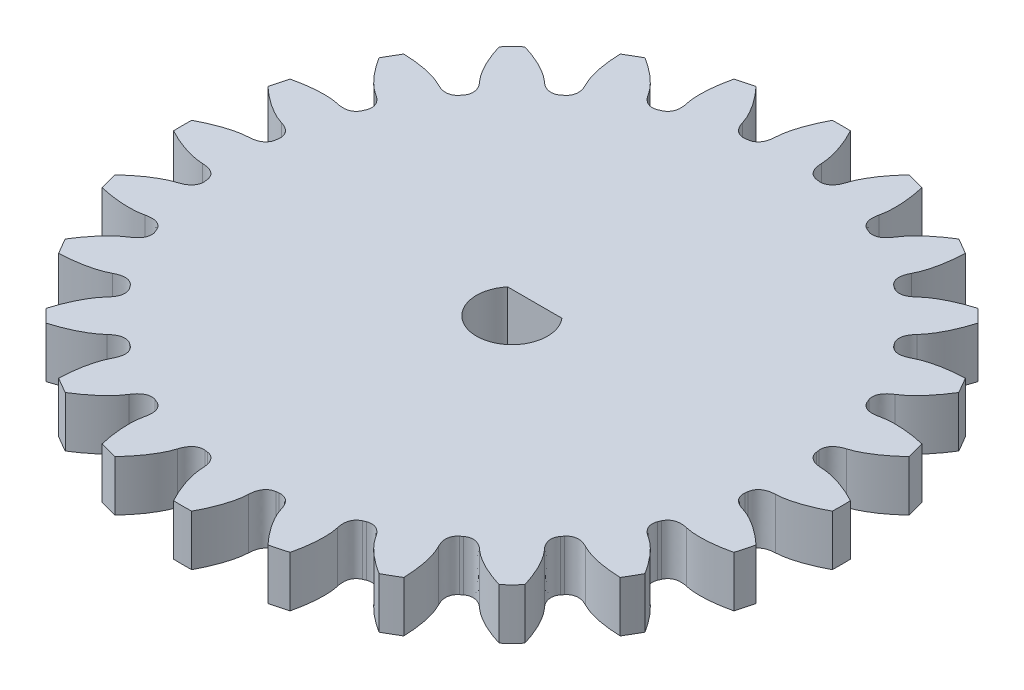
SolidWorks part; units mm, degrees
ref_plane "Спереди" through (0, 0, 0) normal (0, 0, 1) x (1, 0, 0)
ref_plane "Сверху" through (0, 0, 0) normal (0, 1, 0) x (1, 0, 0)
ref_plane "Справа" through (0, 0, 0) normal (1, 0, 0) x (0, 0, -1)
sketch "Эскиз1" plane through (0, 0, 0) normal (0, 1, 0) x (1, 0, 0)
  line L0 (-1.0724, 0.9) -> (1.0724, 0.9)
  arc A3 (-1.0724, 0.9) -> (1.0724, 0.9) centre (0, 0) ccw
  point P1 (0, -1.4)
  line B0 (-14.3, 0) -> (14.3, 0) construction
  line B1 (0, -14.3) -> (0, 14.3) construction
  arc B2 (0.3577, 12.9951) -> (-0.3577, 12.9951) centre (0, 0) ccw
  arc B3 (-1.346, 10.6654) -> (-1.4603, 10.6504) centre (0, 0) ccw
  arc B4 (-3.0178, 12.6449) -> (-3.7089, 12.4597) centre (0, 0) ccw
  arc B5 (-4.0605, 9.9536) -> (-4.1671, 9.9095) centre (0, 0) ccw
  arc B6 (-6.1877, 11.4329) -> (-6.8073, 11.0752) centre (0, 0) ccw
  arc B7 (-6.4984, 8.5635) -> (-6.5898, 8.4933) centre (0, 0) ccw
  arc B8 (-8.936, 9.4419) -> (-9.4419, 8.936) centre (0, 0) ccw
  arc B9 (-8.4933, 6.5898) -> (-8.5635, 6.4984) centre (0, 0) ccw
  arc B10 (-11.0752, 6.8073) -> (-11.4329, 6.1877) centre (0, 0) ccw
  arc B11 (-9.9095, 4.1671) -> (-9.9536, 4.0605) centre (0, 0) ccw
  arc B12 (-12.4597, 3.7089) -> (-12.6449, 3.0178) centre (0, 0) ccw
  arc B13 (-10.6504, 1.4603) -> (-10.6654, 1.346) centre (0, 0) ccw
  arc B14 (-12.9951, 0.3577) -> (-12.9951, -0.3577) centre (0, 0) ccw
  arc B15 (-10.6654, -1.346) -> (-10.6504, -1.4603) centre (0, 0) ccw
  arc B16 (-12.6449, -3.0178) -> (-12.4597, -3.7089) centre (0, 0) ccw
  arc B17 (-9.9536, -4.0605) -> (-9.9095, -4.1671) centre (0, 0) ccw
  arc B18 (-11.4329, -6.1877) -> (-11.0752, -6.8073) centre (0, 0) ccw
  arc B19 (-8.5635, -6.4984) -> (-8.4933, -6.5898) centre (0, 0) ccw
  arc B20 (-9.4419, -8.936) -> (-8.936, -9.4419) centre (0, 0) ccw
  arc B21 (-6.5898, -8.4933) -> (-6.4984, -8.5635) centre (0, 0) ccw
  arc B22 (-6.8073, -11.0752) -> (-6.1877, -11.4329) centre (0, 0) ccw
  arc B23 (-4.1671, -9.9095) -> (-4.0605, -9.9536) centre (0, 0) ccw
  arc B24 (-3.7089, -12.4597) -> (-3.0178, -12.6449) centre (0, 0) ccw
  arc B25 (-1.4603, -10.6504) -> (-1.346, -10.6654) centre (0, 0) ccw
  arc B26 (-0.3577, -12.9951) -> (0.3577, -12.9951) centre (0, 0) ccw
  arc B27 (1.346, -10.6654) -> (1.4603, -10.6504) centre (0, 0) ccw
  arc B28 (3.0178, -12.6449) -> (3.7089, -12.4597) centre (0, 0) ccw
  arc B29 (4.0605, -9.9536) -> (4.1671, -9.9095) centre (0, 0) ccw
  arc B30 (6.1877, -11.4329) -> (6.8073, -11.0752) centre (0, 0) ccw
  arc B31 (6.4984, -8.5635) -> (6.5898, -8.4933) centre (0, 0) ccw
  arc B32 (8.936, -9.4419) -> (9.4419, -8.936) centre (0, 0) ccw
  arc B33 (8.4933, -6.5898) -> (8.5635, -6.4984) centre (0, 0) ccw
  arc B34 (11.0752, -6.8073) -> (11.4329, -6.1877) centre (0, 0) ccw
  arc B35 (9.9095, -4.1671) -> (9.9536, -4.0605) centre (0, 0) ccw
  arc B36 (12.4597, -3.7089) -> (12.6449, -3.0178) centre (0, 0) ccw
  arc B37 (10.6504, -1.4603) -> (10.6654, -1.346) centre (0, 0) ccw
  arc B38 (12.9951, -0.3577) -> (12.9951, 0.3577) centre (0, 0) ccw
  arc B39 (10.6654, 1.346) -> (10.6504, 1.4603) centre (0, 0) ccw
  arc B40 (12.6449, 3.0178) -> (12.4597, 3.7089) centre (0, 0) ccw
  arc B41 (9.9536, 4.0605) -> (9.9095, 4.1671) centre (0, 0) ccw
  arc B42 (11.4329, 6.1877) -> (11.0752, 6.8073) centre (0, 0) ccw
  arc B43 (8.5635, 6.4984) -> (8.4933, 6.5898) centre (0, 0) ccw
  arc B44 (9.4419, 8.936) -> (8.936, 9.4419) centre (0, 0) ccw
  arc B45 (6.5898, 8.4933) -> (6.4984, 8.5635) centre (0, 0) ccw
  arc B46 (6.8073, 11.0752) -> (6.1877, 11.4329) centre (0, 0) ccw
  arc B47 (4.1671, 9.9095) -> (4.0605, 9.9536) centre (0, 0) ccw
  arc B48 (3.7089, 12.4597) -> (3.0178, 12.6449) centre (0, 0) ccw
  arc B49 (1.4603, 10.6504) -> (1.346, 10.6654) centre (0, 0) ccw
  circle B50 centre (0, 0) radius 12 construction
  spline B51 degree 3 poles (0.9058, 11.3017) (0.9058, 11.2304) (0.9138, 11.1608) (0.9299, 11.0929) (0.9396, 11.0522) (0.9513, 11.0113) (0.9676, 10.9727) (0.9799, 10.9437) (0.994, 10.915) (1.0107, 10.8883) (1.0248, 10.8656) (1.0406, 10.8436) (1.058, 10.8234) (1.0738, 10.805) (1.091, 10.7875) (1.1093, 10.7717) (1.1266, 10.7569) (1.1451, 10.7431) (1.1643, 10.7309) (1.1829, 10.7192) (1.2025, 10.7087) (1.2225, 10.6998) (1.2421, 10.6911) (1.2626, 10.6838) (1.2833, 10.678) (1.3038, 10.6723) (1.3247, 10.6681) (1.346, 10.6654) knots 0 0 0 0 1 1 1 2 2 2 3 3 3 4 4 4 5 5 5 6 6 6 7 7 7 8 8 8 9 9 9 9
  spline B52 degree 3 poles (-0.9058, 11.3017) (-0.9058, 11.2304) (-0.9138, 11.1608) (-0.9299, 11.0929) (-0.9396, 11.0522) (-0.9513, 11.0113) (-0.9676, 10.9727) (-0.9799, 10.9437) (-0.994, 10.915) (-1.0107, 10.8883) (-1.0248, 10.8656) (-1.0406, 10.8436) (-1.058, 10.8234) (-1.0738, 10.805) (-1.091, 10.7875) (-1.1093, 10.7717) (-1.1266, 10.7569) (-1.1451, 10.7431) (-1.1643, 10.7309) (-1.1829, 10.7192) (-1.2025, 10.7087) (-1.2225, 10.6998) (-1.2421, 10.6911) (-1.2626, 10.6838) (-1.2833, 10.678) (-1.3038, 10.6723) (-1.3247, 10.6681) (-1.346, 10.6654) knots 0 0 0 0 1 1 1 2 2 2 3 3 3 4 4 4 5 5 5 6 6 6 7 7 7 8 8 8 9 9 9 9
  spline B53 degree 3 poles (0.9058, 11.3017) (0.9032, 11.3642) (0.898, 11.4263) (0.8903, 11.4882) (0.8824, 11.551) (0.8712, 11.6136) (0.8589, 11.6757) (0.8463, 11.7389) (0.8314, 11.8016) (0.8153, 11.864) (0.7989, 11.9273) (0.7806, 11.9902) (0.7612, 12.0526) (0.7414, 12.116) (0.72, 12.179) (0.6975, 12.2415) (0.6746, 12.3049) (0.6503, 12.3678) (0.6249, 12.4303) (0.5991, 12.4937) (0.572, 12.5566) (0.5439, 12.6189) (0.5153, 12.6822) (0.4855, 12.745) (0.4547, 12.8073) (0.4235, 12.8704) (0.3912, 12.933) (0.3577, 12.9951) knots 0 0 0 0 1 1 1 2 2 2 3 3 3 4 4 4 5 5 5 6 6 6 7 7 7 8 8 8 9 9 9 9
  spline B54 degree 3 poles (-0.9058, 11.3017) (-0.9032, 11.3642) (-0.898, 11.4263) (-0.8903, 11.4882) (-0.8824, 11.551) (-0.8712, 11.6136) (-0.8589, 11.6757) (-0.8463, 11.7389) (-0.8314, 11.8016) (-0.8153, 11.864) (-0.7989, 11.9273) (-0.7806, 11.9902) (-0.7612, 12.0526) (-0.7414, 12.116) (-0.72, 12.179) (-0.6975, 12.2415) (-0.6746, 12.3049) (-0.6503, 12.3678) (-0.6249, 12.4303) (-0.5991, 12.4937) (-0.572, 12.5566) (-0.5439, 12.6189) (-0.5153, 12.6822) (-0.4855, 12.745) (-0.4547, 12.8073) (-0.4235, 12.8704) (-0.3912, 12.933) (-0.3577, 12.9951) knots 0 0 0 0 1 1 1 2 2 2 3 3 3 4 4 4 5 5 5 6 6 6 7 7 7 8 8 8 9 9 9 9
  spline B55 degree 3 poles (-2.0502, 11.151) (-2.0317, 11.0822) (-2.0059, 11.017) (-1.9728, 10.9556) (-1.9529, 10.9188) (-1.931, 10.8823) (-1.9053, 10.8493) (-1.886, 10.8244) (-1.8649, 10.8004) (-1.8419, 10.7789) (-1.8224, 10.7606) (-1.8014, 10.7435) (-1.7793, 10.7284) (-1.7594, 10.7148) (-1.7382, 10.7023) (-1.7164, 10.6918) (-1.6959, 10.6819) (-1.6745, 10.6734) (-1.6527, 10.6666) (-1.6318, 10.6601) (-1.6101, 10.655) (-1.5885, 10.6516) (-1.5672, 10.6483) (-1.5456, 10.6465) (-1.5241, 10.6463) (-1.5028, 10.6461) (-1.4816, 10.6475) (-1.4603, 10.6504) knots 0 0 0 0 1 1 1 2 2 2 3 3 3 4 4 4 5 5 5 6 6 6 7 7 7 8 8 8 9 9 9 9
  spline B56 degree 3 poles (-3.8, 10.6822) (-3.7815, 10.6133) (-3.7713, 10.544) (-3.7693, 10.4743) (-3.7681, 10.4325) (-3.7688, 10.3898) (-3.7746, 10.3484) (-3.7789, 10.3172) (-3.7852, 10.2858) (-3.7943, 10.2557) (-3.8021, 10.2302) (-3.8117, 10.2048) (-3.8232, 10.1807) (-3.8337, 10.1589) (-3.8458, 10.1376) (-3.8595, 10.1176) (-3.8723, 10.0988) (-3.8866, 10.0806) (-3.902, 10.0639) (-3.9169, 10.0478) (-3.9331, 10.0326) (-3.9502, 10.0188) (-3.9669, 10.0053) (-3.9848, 9.9929) (-4.0032, 9.982) (-4.0216, 9.9712) (-4.0406, 9.9618) (-4.0605, 9.9536) knots 0 0 0 0 1 1 1 2 2 2 3 3 3 4 4 4 5 5 5 6 6 6 7 7 7 8 8 8 9 9 9 9
  spline B57 degree 3 poles (-2.0502, 11.151) (-2.0689, 11.2107) (-2.09, 11.2694) (-2.1134, 11.3271) (-2.1373, 11.3858) (-2.1643, 11.4434) (-2.1923, 11.5002) (-2.2208, 11.5579) (-2.2514, 11.6147) (-2.2831, 11.6707) (-2.3153, 11.7276) (-2.3493, 11.7837) (-2.3842, 11.8389) (-2.4197, 11.8951) (-2.4567, 11.9503) (-2.4946, 12.0049) (-2.5331, 12.0602) (-2.5729, 12.1147) (-2.6136, 12.1685) (-2.6549, 12.223) (-2.6974, 12.2768) (-2.7407, 12.3297) (-2.7847, 12.3835) (-2.8297, 12.4364) (-2.8755, 12.4885) (-2.9221, 12.5415) (-2.9695, 12.5936) (-3.0178, 12.6449) knots 0 0 0 0 1 1 1 2 2 2 3 3 3 4 4 4 5 5 5 6 6 6 7 7 7 8 8 8 9 9 9 9
  spline B58 degree 3 poles (-3.8, 10.6822) (-3.8136, 10.7432) (-3.8247, 10.8046) (-3.8333, 10.8663) (-3.842, 10.929) (-3.8474, 10.9924) (-3.8515, 11.0556) (-3.8557, 11.1198) (-3.8576, 11.1843) (-3.8581, 11.2487) (-3.8587, 11.3141) (-3.8573, 11.3796) (-3.8547, 11.4449) (-3.852, 11.5113) (-3.8476, 11.5776) (-3.8421, 11.6438) (-3.8364, 11.711) (-3.8292, 11.7781) (-3.8208, 11.845) (-3.8123, 11.9129) (-3.8024, 11.9807) (-3.7914, 12.0482) (-3.7802, 12.1167) (-3.7676, 12.1851) (-3.754, 12.2532) (-3.7402, 12.3223) (-3.7251, 12.3911) (-3.7089, 12.4597) knots 0 0 0 0 1 1 1 2 2 2 3 3 3 4 4 4 5 5 5 6 6 6 7 7 7 8 8 8 9 9 9 9
  spline B59 degree 3 poles (-4.8664, 10.2404) (-4.8308, 10.1787) (-4.789, 10.1225) (-4.7411, 10.0717) (-4.7124, 10.0413) (-4.6817, 10.0117) (-4.6484, 9.9865) (-4.6233, 9.9675) (-4.5967, 9.9497) (-4.5689, 9.9349) (-4.5453, 9.9223) (-4.5206, 9.9111) (-4.4954, 9.9023) (-4.4726, 9.8943) (-4.4489, 9.8878) (-4.4252, 9.8833) (-4.4028, 9.879) (-4.3799, 9.8763) (-4.3571, 9.8754) (-4.3352, 9.8745) (-4.313, 9.8752) (-4.2912, 9.8776) (-4.2698, 9.8798) (-4.2484, 9.8837) (-4.2276, 9.8891) (-4.2071, 9.8944) (-4.1869, 9.9012) (-4.1671, 9.9095) knots 0 0 0 0 1 1 1 2 2 2 3 3 3 4 4 4 5 5 5 6 6 6 7 7 7 8 8 8 9 9 9 9
  spline B60 degree 3 poles (-6.4353, 9.3347) (-6.3996, 9.2729) (-6.3718, 9.2086) (-6.3518, 9.1418) (-6.3398, 9.1017) (-6.3295, 9.0604) (-6.3243, 9.0188) (-6.3204, 8.9876) (-6.3184, 8.9557) (-6.3194, 8.9242) (-6.3203, 8.8975) (-6.323, 8.8706) (-6.3279, 8.8443) (-6.3324, 8.8205) (-6.3386, 8.7968) (-6.3466, 8.7739) (-6.3541, 8.7524) (-6.3632, 8.7312) (-6.3738, 8.7111) (-6.384, 8.6917) (-6.3957, 8.6728) (-6.4086, 8.655) (-6.4213, 8.6377) (-6.4353, 8.6211) (-6.4504, 8.6058) (-6.4653, 8.5906) (-6.4813, 8.5765) (-6.4984, 8.5635) knots 0 0 0 0 1 1 1 2 2 2 3 3 3 4 4 4 5 5 5 6 6 6 7 7 7 8 8 8 9 9 9 9
  spline B61 degree 3 poles (-4.8664, 10.2404) (-4.8999, 10.2932) (-4.9355, 10.3445) (-4.9731, 10.3942) (-5.0113, 10.4447) (-5.0523, 10.4933) (-5.0941, 10.5409) (-5.1365, 10.5893) (-5.1808, 10.6362) (-5.2259, 10.6822) (-5.2718, 10.7288) (-5.319, 10.7741) (-5.3671, 10.8185) (-5.4159, 10.8635) (-5.4659, 10.9073) (-5.5167, 10.9502) (-5.5682, 10.9937) (-5.6207, 11.036) (-5.674, 11.0774) (-5.728, 11.1194) (-5.7829, 11.1603) (-5.8385, 11.2003) (-5.8949, 11.2408) (-5.9521, 11.2803) (-6.0098, 11.3188) (-6.0685, 11.3578) (-6.1278, 11.3959) (-6.1877, 11.4329) knots 0 0 0 0 1 1 1 2 2 2 3 3 3 4 4 4 5 5 5 6 6 6 7 7 7 8 8 8 9 9 9 9
  spline B62 degree 3 poles (-6.4353, 9.3347) (-6.4642, 9.3901) (-6.4908, 9.4465) (-6.5151, 9.5039) (-6.5397, 9.5623) (-6.5613, 9.622) (-6.5817, 9.6821) (-6.6024, 9.743) (-6.6209, 9.8048) (-6.638, 9.8669) (-6.6555, 9.9299) (-6.6711, 9.9935) (-6.6855, 10.0573) (-6.7001, 10.1221) (-6.713, 10.1873) (-6.7248, 10.2527) (-6.7367, 10.319) (-6.7471, 10.3857) (-6.7563, 10.4525) (-6.7657, 10.5203) (-6.7737, 10.5883) (-6.7805, 10.6564) (-6.7874, 10.7255) (-6.793, 10.7948) (-6.7974, 10.8641) (-6.8019, 10.9344) (-6.8053, 11.0047) (-6.8073, 11.0752) knots 0 0 0 0 1 1 1 2 2 2 3 3 3 4 4 4 5 5 5 6 6 6 7 7 7 8 8 8 9 9 9 9
  spline B63 degree 3 poles (-7.351, 8.632) (-7.3006, 8.5816) (-7.2457, 8.5381) (-7.1863, 8.5015) (-7.1507, 8.4795) (-7.1134, 8.4588) (-7.0747, 8.4431) (-7.0455, 8.4312) (-7.0152, 8.421) (-6.9845, 8.4138) (-6.9585, 8.4078) (-6.9318, 8.4034) (-6.9052, 8.4014) (-6.881, 8.3996) (-6.8565, 8.3994) (-6.8324, 8.4012) (-6.8097, 8.4029) (-6.7868, 8.4062) (-6.7646, 8.4112) (-6.7432, 8.416) (-6.7219, 8.4224) (-6.7015, 8.4304) (-6.6814, 8.4381) (-6.6618, 8.4474) (-6.6431, 8.4579) (-6.6246, 8.4684) (-6.6068, 8.4802) (-6.5898, 8.4933) knots 0 0 0 0 1 1 1 2 2 2 3 3 3 4 4 4 5 5 5 6 6 6 7 7 7 8 8 8 9 9 9 9
  spline B64 degree 3 poles (-8.632, 7.351) (-8.5816, 7.3006) (-8.5381, 7.2457) (-8.5015, 7.1863) (-8.4795, 7.1507) (-8.4588, 7.1134) (-8.4431, 7.0747) (-8.4312, 7.0455) (-8.421, 7.0152) (-8.4138, 6.9845) (-8.4078, 6.9585) (-8.4034, 6.9318) (-8.4014, 6.9052) (-8.3996, 6.881) (-8.3994, 6.8565) (-8.4012, 6.8324) (-8.4029, 6.8097) (-8.4062, 6.7868) (-8.4112, 6.7646) (-8.416, 6.7432) (-8.4224, 6.7219) (-8.4304, 6.7015) (-8.4381, 6.6814) (-8.4474, 6.6618) (-8.4579, 6.6431) (-8.4684, 6.6246) (-8.4802, 6.6068) (-8.4933, 6.5898) knots 0 0 0 0 1 1 1 2 2 2 3 3 3 4 4 4 5 5 5 6 6 6 7 7 7 8 8 8 9 9 9 9
  spline B65 degree 3 poles (-7.351, 8.632) (-7.3971, 8.6743) (-7.4447, 8.7146) (-7.4938, 8.7529) (-7.5438, 8.7918) (-7.596, 8.8281) (-7.6487, 8.8633) (-7.7022, 8.8991) (-7.7571, 8.9329) (-7.8126, 8.9656) (-7.869, 8.9988) (-7.9263, 9.0303) (-7.9843, 9.0607) (-8.0431, 9.0916) (-8.1027, 9.121) (-8.1628, 9.1492) (-8.2238, 9.1779) (-8.2855, 9.2052) (-8.3477, 9.2314) (-8.4107, 9.258) (-8.4744, 9.2833) (-8.5384, 9.3075) (-8.6033, 9.3321) (-8.6688, 9.3554) (-8.7346, 9.3776) (-8.8013, 9.4002) (-8.8684, 9.4216) (-8.936, 9.4419) knots 0 0 0 0 1 1 1 2 2 2 3 3 3 4 4 4 5 5 5 6 6 6 7 7 7 8 8 8 9 9 9 9
  spline B66 degree 3 poles (-8.632, 7.351) (-8.6743, 7.3971) (-8.7146, 7.4447) (-8.7529, 7.4938) (-8.7918, 7.5438) (-8.8281, 7.596) (-8.8633, 7.6487) (-8.8991, 7.7022) (-8.9329, 7.7571) (-8.9656, 7.8126) (-8.9988, 7.869) (-9.0303, 7.9263) (-9.0607, 7.9843) (-9.0916, 8.0431) (-9.121, 8.1027) (-9.1492, 8.1628) (-9.1779, 8.2238) (-9.2052, 8.2855) (-9.2314, 8.3477) (-9.258, 8.4107) (-9.2833, 8.4744) (-9.3075, 8.5384) (-9.3321, 8.6033) (-9.3554, 8.6688) (-9.3776, 8.7346) (-9.4002, 8.8013) (-9.4216, 8.8684) (-9.4419, 8.936) knots 0 0 0 0 1 1 1 2 2 2 3 3 3 4 4 4 5 5 5 6 6 6 7 7 7 8 8 8 9 9 9 9
  spline B67 degree 3 poles (-9.3347, 6.4353) (-9.2729, 6.3996) (-9.2086, 6.3718) (-9.1418, 6.3518) (-9.1017, 6.3398) (-9.0604, 6.3295) (-9.0188, 6.3243) (-8.9876, 6.3204) (-8.9557, 6.3184) (-8.9242, 6.3194) (-8.8975, 6.3203) (-8.8706, 6.323) (-8.8443, 6.3279) (-8.8205, 6.3324) (-8.7968, 6.3386) (-8.7739, 6.3466) (-8.7524, 6.3541) (-8.7312, 6.3632) (-8.7111, 6.3738) (-8.6917, 6.384) (-8.6728, 6.3957) (-8.655, 6.4086) (-8.6377, 6.4213) (-8.6211, 6.4353) (-8.6058, 6.4504) (-8.5906, 6.4653) (-8.5765, 6.4813) (-8.5635, 6.4984) knots 0 0 0 0 1 1 1 2 2 2 3 3 3 4 4 4 5 5 5 6 6 6 7 7 7 8 8 8 9 9 9 9
  spline B68 degree 3 poles (-10.2404, 4.8664) (-10.1787, 4.8308) (-10.1225, 4.789) (-10.0717, 4.7411) (-10.0413, 4.7124) (-10.0117, 4.6817) (-9.9865, 4.6484) (-9.9675, 4.6233) (-9.9497, 4.5967) (-9.9349, 4.5689) (-9.9223, 4.5453) (-9.9111, 4.5206) (-9.9023, 4.4954) (-9.8943, 4.4726) (-9.8878, 4.4489) (-9.8833, 4.4252) (-9.879, 4.4028) (-9.8763, 4.3799) (-9.8754, 4.3571) (-9.8745, 4.3352) (-9.8752, 4.313) (-9.8776, 4.2912) (-9.8798, 4.2698) (-9.8837, 4.2484) (-9.8891, 4.2276) (-9.8944, 4.2071) (-9.9012, 4.1869) (-9.9095, 4.1671) knots 0 0 0 0 1 1 1 2 2 2 3 3 3 4 4 4 5 5 5 6 6 6 7 7 7 8 8 8 9 9 9 9
  spline B69 degree 3 poles (-9.3347, 6.4353) (-9.3901, 6.4642) (-9.4465, 6.4908) (-9.5039, 6.5151) (-9.5623, 6.5397) (-9.622, 6.5613) (-9.6821, 6.5817) (-9.743, 6.6024) (-9.8048, 6.6209) (-9.8669, 6.638) (-9.9299, 6.6555) (-9.9935, 6.6711) (-10.0573, 6.6855) (-10.1221, 6.7001) (-10.1873, 6.713) (-10.2527, 6.7248) (-10.319, 6.7367) (-10.3857, 6.7471) (-10.4525, 6.7563) (-10.5203, 6.7657) (-10.5883, 6.7737) (-10.6564, 6.7805) (-10.7255, 6.7874) (-10.7948, 6.793) (-10.8641, 6.7974) (-10.9344, 6.8019) (-11.0047, 6.8053) (-11.0752, 6.8073) knots 0 0 0 0 1 1 1 2 2 2 3 3 3 4 4 4 5 5 5 6 6 6 7 7 7 8 8 8 9 9 9 9
  spline B70 degree 3 poles (-10.2404, 4.8664) (-10.2932, 4.8999) (-10.3445, 4.9355) (-10.3942, 4.9731) (-10.4447, 5.0113) (-10.4933, 5.0523) (-10.5409, 5.0941) (-10.5893, 5.1365) (-10.6362, 5.1808) (-10.6822, 5.2259) (-10.7288, 5.2718) (-10.7741, 5.319) (-10.8185, 5.3671) (-10.8635, 5.4159) (-10.9073, 5.4659) (-10.9502, 5.5167) (-10.9937, 5.5682) (-11.036, 5.6207) (-11.0774, 5.674) (-11.1194, 5.728) (-11.1603, 5.7829) (-11.2003, 5.8385) (-11.2408, 5.8949) (-11.2803, 5.9521) (-11.3188, 6.0098) (-11.3578, 6.0685) (-11.3959, 6.1278) (-11.4329, 6.1877) knots 0 0 0 0 1 1 1 2 2 2 3 3 3 4 4 4 5 5 5 6 6 6 7 7 7 8 8 8 9 9 9 9
  spline B71 degree 3 poles (-10.6822, 3.8) (-10.6133, 3.7815) (-10.544, 3.7713) (-10.4743, 3.7693) (-10.4325, 3.7681) (-10.3898, 3.7688) (-10.3484, 3.7746) (-10.3172, 3.7789) (-10.2858, 3.7852) (-10.2557, 3.7943) (-10.2302, 3.8021) (-10.2048, 3.8117) (-10.1807, 3.8232) (-10.1589, 3.8337) (-10.1376, 3.8458) (-10.1176, 3.8595) (-10.0988, 3.8723) (-10.0806, 3.8866) (-10.0639, 3.902) (-10.0478, 3.9169) (-10.0326, 3.9331) (-10.0188, 3.9502) (-10.0053, 3.9669) (-9.9929, 3.9848) (-9.982, 4.0032) (-9.9712, 4.0216) (-9.9618, 4.0406) (-9.9536, 4.0605) knots 0 0 0 0 1 1 1 2 2 2 3 3 3 4 4 4 5 5 5 6 6 6 7 7 7 8 8 8 9 9 9 9
  spline B72 degree 3 poles (-11.151, 2.0502) (-11.0822, 2.0317) (-11.017, 2.0059) (-10.9556, 1.9728) (-10.9188, 1.9529) (-10.8823, 1.931) (-10.8493, 1.9053) (-10.8244, 1.886) (-10.8004, 1.8649) (-10.7789, 1.8419) (-10.7606, 1.8224) (-10.7435, 1.8014) (-10.7284, 1.7793) (-10.7148, 1.7594) (-10.7023, 1.7382) (-10.6918, 1.7164) (-10.6819, 1.6959) (-10.6734, 1.6745) (-10.6666, 1.6527) (-10.6601, 1.6318) (-10.655, 1.6101) (-10.6516, 1.5885) (-10.6483, 1.5672) (-10.6465, 1.5456) (-10.6463, 1.5241) (-10.6461, 1.5028) (-10.6475, 1.4816) (-10.6504, 1.4603) knots 0 0 0 0 1 1 1 2 2 2 3 3 3 4 4 4 5 5 5 6 6 6 7 7 7 8 8 8 9 9 9 9
  spline B73 degree 3 poles (-10.6822, 3.8) (-10.7432, 3.8136) (-10.8046, 3.8247) (-10.8663, 3.8333) (-10.929, 3.842) (-10.9924, 3.8474) (-11.0556, 3.8515) (-11.1198, 3.8557) (-11.1843, 3.8576) (-11.2487, 3.8581) (-11.3141, 3.8587) (-11.3796, 3.8573) (-11.4449, 3.8547) (-11.5113, 3.852) (-11.5776, 3.8476) (-11.6438, 3.8421) (-11.711, 3.8364) (-11.7781, 3.8292) (-11.845, 3.8208) (-11.9129, 3.8123) (-11.9807, 3.8024) (-12.0482, 3.7914) (-12.1167, 3.7802) (-12.1851, 3.7676) (-12.2532, 3.754) (-12.3223, 3.7402) (-12.3911, 3.7251) (-12.4597, 3.7089) knots 0 0 0 0 1 1 1 2 2 2 3 3 3 4 4 4 5 5 5 6 6 6 7 7 7 8 8 8 9 9 9 9
  spline B74 degree 3 poles (-11.151, 2.0502) (-11.2107, 2.0689) (-11.2694, 2.09) (-11.3271, 2.1134) (-11.3858, 2.1373) (-11.4434, 2.1643) (-11.5002, 2.1923) (-11.5579, 2.2208) (-11.6147, 2.2514) (-11.6707, 2.2831) (-11.7276, 2.3153) (-11.7837, 2.3493) (-11.8389, 2.3842) (-11.8951, 2.4197) (-11.9503, 2.4567) (-12.0049, 2.4946) (-12.0602, 2.5331) (-12.1147, 2.5729) (-12.1685, 2.6136) (-12.223, 2.6549) (-12.2768, 2.6974) (-12.3297, 2.7407) (-12.3835, 2.7847) (-12.4364, 2.8297) (-12.4885, 2.8755) (-12.5415, 2.9221) (-12.5936, 2.9695) (-12.6449, 3.0178) knots 0 0 0 0 1 1 1 2 2 2 3 3 3 4 4 4 5 5 5 6 6 6 7 7 7 8 8 8 9 9 9 9
  spline B75 degree 3 poles (-11.3017, 0.9058) (-11.2304, 0.9058) (-11.1608, 0.9138) (-11.0929, 0.9299) (-11.0522, 0.9396) (-11.0113, 0.9513) (-10.9727, 0.9676) (-10.9437, 0.9799) (-10.915, 0.994) (-10.8883, 1.0107) (-10.8656, 1.0248) (-10.8436, 1.0406) (-10.8234, 1.058) (-10.805, 1.0738) (-10.7875, 1.091) (-10.7717, 1.1093) (-10.7569, 1.1266) (-10.7431, 1.1451) (-10.7309, 1.1643) (-10.7192, 1.1829) (-10.7087, 1.2025) (-10.6998, 1.2225) (-10.6911, 1.2421) (-10.6838, 1.2626) (-10.678, 1.2833) (-10.6723, 1.3038) (-10.6681, 1.3247) (-10.6654, 1.346) knots 0 0 0 0 1 1 1 2 2 2 3 3 3 4 4 4 5 5 5 6 6 6 7 7 7 8 8 8 9 9 9 9
  spline B76 degree 3 poles (-11.3017, -0.9058) (-11.2304, -0.9058) (-11.1608, -0.9138) (-11.0929, -0.9299) (-11.0522, -0.9396) (-11.0113, -0.9513) (-10.9727, -0.9676) (-10.9437, -0.9799) (-10.915, -0.994) (-10.8883, -1.0107) (-10.8656, -1.0248) (-10.8436, -1.0406) (-10.8234, -1.058) (-10.805, -1.0738) (-10.7875, -1.091) (-10.7717, -1.1093) (-10.7569, -1.1266) (-10.7431, -1.1451) (-10.7309, -1.1643) (-10.7192, -1.1829) (-10.7087, -1.2025) (-10.6998, -1.2225) (-10.6911, -1.2421) (-10.6838, -1.2626) (-10.678, -1.2833) (-10.6723, -1.3038) (-10.6681, -1.3247) (-10.6654, -1.346) knots 0 0 0 0 1 1 1 2 2 2 3 3 3 4 4 4 5 5 5 6 6 6 7 7 7 8 8 8 9 9 9 9
  spline B77 degree 3 poles (-11.3017, 0.9058) (-11.3642, 0.9032) (-11.4263, 0.898) (-11.4882, 0.8903) (-11.551, 0.8824) (-11.6136, 0.8712) (-11.6757, 0.8589) (-11.7389, 0.8463) (-11.8016, 0.8314) (-11.864, 0.8153) (-11.9273, 0.7989) (-11.9902, 0.7806) (-12.0526, 0.7612) (-12.116, 0.7414) (-12.179, 0.72) (-12.2415, 0.6975) (-12.3049, 0.6746) (-12.3678, 0.6503) (-12.4303, 0.6249) (-12.4937, 0.5991) (-12.5566, 0.572) (-12.6189, 0.5439) (-12.6822, 0.5153) (-12.745, 0.4855) (-12.8073, 0.4547) (-12.8704, 0.4235) (-12.933, 0.3912) (-12.9951, 0.3577) knots 0 0 0 0 1 1 1 2 2 2 3 3 3 4 4 4 5 5 5 6 6 6 7 7 7 8 8 8 9 9 9 9
  spline B78 degree 3 poles (-11.3017, -0.9058) (-11.3642, -0.9032) (-11.4263, -0.898) (-11.4882, -0.8903) (-11.551, -0.8824) (-11.6136, -0.8712) (-11.6757, -0.8589) (-11.7389, -0.8463) (-11.8016, -0.8314) (-11.864, -0.8153) (-11.9273, -0.7989) (-11.9902, -0.7806) (-12.0526, -0.7612) (-12.116, -0.7414) (-12.179, -0.72) (-12.2415, -0.6975) (-12.3049, -0.6746) (-12.3678, -0.6503) (-12.4303, -0.6249) (-12.4937, -0.5991) (-12.5566, -0.572) (-12.6189, -0.5439) (-12.6822, -0.5153) (-12.745, -0.4855) (-12.8073, -0.4547) (-12.8704, -0.4235) (-12.933, -0.3912) (-12.9951, -0.3577) knots 0 0 0 0 1 1 1 2 2 2 3 3 3 4 4 4 5 5 5 6 6 6 7 7 7 8 8 8 9 9 9 9
  spline B79 degree 3 poles (-11.151, -2.0502) (-11.0822, -2.0317) (-11.017, -2.0059) (-10.9556, -1.9728) (-10.9188, -1.9529) (-10.8823, -1.931) (-10.8493, -1.9053) (-10.8244, -1.886) (-10.8004, -1.8649) (-10.7789, -1.8419) (-10.7606, -1.8224) (-10.7435, -1.8014) (-10.7284, -1.7793) (-10.7148, -1.7594) (-10.7023, -1.7382) (-10.6918, -1.7164) (-10.6819, -1.6959) (-10.6734, -1.6745) (-10.6666, -1.6527) (-10.6601, -1.6318) (-10.655, -1.6101) (-10.6516, -1.5885) (-10.6483, -1.5672) (-10.6465, -1.5456) (-10.6463, -1.5241) (-10.6461, -1.5028) (-10.6475, -1.4816) (-10.6504, -1.4603) knots 0 0 0 0 1 1 1 2 2 2 3 3 3 4 4 4 5 5 5 6 6 6 7 7 7 8 8 8 9 9 9 9
  spline B80 degree 3 poles (-10.6822, -3.8) (-10.6133, -3.7815) (-10.544, -3.7713) (-10.4743, -3.7693) (-10.4325, -3.7681) (-10.3898, -3.7688) (-10.3484, -3.7746) (-10.3172, -3.7789) (-10.2858, -3.7852) (-10.2557, -3.7943) (-10.2302, -3.8021) (-10.2048, -3.8117) (-10.1807, -3.8232) (-10.1589, -3.8337) (-10.1376, -3.8458) (-10.1176, -3.8595) (-10.0988, -3.8723) (-10.0806, -3.8866) (-10.0639, -3.902) (-10.0478, -3.9169) (-10.0326, -3.9331) (-10.0188, -3.9502) (-10.0053, -3.9669) (-9.9929, -3.9848) (-9.982, -4.0032) (-9.9712, -4.0216) (-9.9618, -4.0406) (-9.9536, -4.0605) knots 0 0 0 0 1 1 1 2 2 2 3 3 3 4 4 4 5 5 5 6 6 6 7 7 7 8 8 8 9 9 9 9
  spline B81 degree 3 poles (-11.151, -2.0502) (-11.2107, -2.0689) (-11.2694, -2.09) (-11.3271, -2.1134) (-11.3858, -2.1373) (-11.4434, -2.1643) (-11.5002, -2.1923) (-11.5579, -2.2208) (-11.6147, -2.2514) (-11.6707, -2.2831) (-11.7276, -2.3153) (-11.7837, -2.3493) (-11.8389, -2.3842) (-11.8951, -2.4197) (-11.9503, -2.4567) (-12.0049, -2.4946) (-12.0602, -2.5331) (-12.1147, -2.5729) (-12.1685, -2.6136) (-12.223, -2.6549) (-12.2768, -2.6974) (-12.3297, -2.7407) (-12.3835, -2.7847) (-12.4364, -2.8297) (-12.4885, -2.8755) (-12.5415, -2.9221) (-12.5936, -2.9695) (-12.6449, -3.0178) knots 0 0 0 0 1 1 1 2 2 2 3 3 3 4 4 4 5 5 5 6 6 6 7 7 7 8 8 8 9 9 9 9
  spline B82 degree 3 poles (-10.6822, -3.8) (-10.7432, -3.8136) (-10.8046, -3.8247) (-10.8663, -3.8333) (-10.929, -3.842) (-10.9924, -3.8474) (-11.0556, -3.8515) (-11.1198, -3.8557) (-11.1843, -3.8576) (-11.2487, -3.8581) (-11.3141, -3.8587) (-11.3796, -3.8573) (-11.4449, -3.8547) (-11.5113, -3.852) (-11.5776, -3.8476) (-11.6438, -3.8421) (-11.711, -3.8364) (-11.7781, -3.8292) (-11.845, -3.8208) (-11.9129, -3.8123) (-11.9807, -3.8024) (-12.0482, -3.7914) (-12.1167, -3.7802) (-12.1851, -3.7676) (-12.2532, -3.754) (-12.3223, -3.7402) (-12.3911, -3.7251) (-12.4597, -3.7089) knots 0 0 0 0 1 1 1 2 2 2 3 3 3 4 4 4 5 5 5 6 6 6 7 7 7 8 8 8 9 9 9 9
  spline B83 degree 3 poles (-10.2404, -4.8664) (-10.1787, -4.8308) (-10.1225, -4.789) (-10.0717, -4.7411) (-10.0413, -4.7124) (-10.0117, -4.6817) (-9.9865, -4.6484) (-9.9675, -4.6233) (-9.9497, -4.5967) (-9.9349, -4.5689) (-9.9223, -4.5453) (-9.9111, -4.5206) (-9.9023, -4.4954) (-9.8943, -4.4726) (-9.8878, -4.4489) (-9.8833, -4.4252) (-9.879, -4.4028) (-9.8763, -4.3799) (-9.8754, -4.3571) (-9.8745, -4.3352) (-9.8752, -4.313) (-9.8776, -4.2912) (-9.8798, -4.2698) (-9.8837, -4.2484) (-9.8891, -4.2276) (-9.8944, -4.2071) (-9.9012, -4.1869) (-9.9095, -4.1671) knots 0 0 0 0 1 1 1 2 2 2 3 3 3 4 4 4 5 5 5 6 6 6 7 7 7 8 8 8 9 9 9 9
  spline B84 degree 3 poles (-9.3347, -6.4353) (-9.2729, -6.3996) (-9.2086, -6.3718) (-9.1418, -6.3518) (-9.1017, -6.3398) (-9.0604, -6.3295) (-9.0188, -6.3243) (-8.9876, -6.3204) (-8.9557, -6.3184) (-8.9242, -6.3194) (-8.8975, -6.3203) (-8.8706, -6.323) (-8.8443, -6.3279) (-8.8205, -6.3324) (-8.7968, -6.3386) (-8.7739, -6.3466) (-8.7524, -6.3541) (-8.7312, -6.3632) (-8.7111, -6.3738) (-8.6917, -6.384) (-8.6728, -6.3957) (-8.655, -6.4086) (-8.6377, -6.4213) (-8.6211, -6.4353) (-8.6058, -6.4504) (-8.5906, -6.4653) (-8.5765, -6.4813) (-8.5635, -6.4984) knots 0 0 0 0 1 1 1 2 2 2 3 3 3 4 4 4 5 5 5 6 6 6 7 7 7 8 8 8 9 9 9 9
  spline B85 degree 3 poles (-10.2404, -4.8664) (-10.2932, -4.8999) (-10.3445, -4.9355) (-10.3942, -4.9731) (-10.4447, -5.0113) (-10.4933, -5.0523) (-10.5409, -5.0941) (-10.5893, -5.1365) (-10.6362, -5.1808) (-10.6822, -5.2259) (-10.7288, -5.2718) (-10.7741, -5.319) (-10.8185, -5.3671) (-10.8635, -5.4159) (-10.9073, -5.4659) (-10.9502, -5.5167) (-10.9937, -5.5682) (-11.036, -5.6207) (-11.0774, -5.674) (-11.1194, -5.728) (-11.1603, -5.7829) (-11.2003, -5.8385) (-11.2408, -5.8949) (-11.2803, -5.9521) (-11.3188, -6.0098) (-11.3578, -6.0685) (-11.3959, -6.1278) (-11.4329, -6.1877) knots 0 0 0 0 1 1 1 2 2 2 3 3 3 4 4 4 5 5 5 6 6 6 7 7 7 8 8 8 9 9 9 9
  spline B86 degree 3 poles (-9.3347, -6.4353) (-9.3901, -6.4642) (-9.4465, -6.4908) (-9.5039, -6.5151) (-9.5623, -6.5397) (-9.622, -6.5613) (-9.6821, -6.5817) (-9.743, -6.6024) (-9.8048, -6.6209) (-9.8669, -6.638) (-9.9299, -6.6555) (-9.9935, -6.6711) (-10.0573, -6.6855) (-10.1221, -6.7001) (-10.1873, -6.713) (-10.2527, -6.7248) (-10.319, -6.7367) (-10.3857, -6.7471) (-10.4525, -6.7563) (-10.5203, -6.7657) (-10.5883, -6.7737) (-10.6564, -6.7805) (-10.7255, -6.7874) (-10.7948, -6.793) (-10.8641, -6.7974) (-10.9344, -6.8019) (-11.0047, -6.8053) (-11.0752, -6.8073) knots 0 0 0 0 1 1 1 2 2 2 3 3 3 4 4 4 5 5 5 6 6 6 7 7 7 8 8 8 9 9 9 9
  spline B87 degree 3 poles (-8.632, -7.351) (-8.5816, -7.3006) (-8.5381, -7.2457) (-8.5015, -7.1863) (-8.4795, -7.1507) (-8.4588, -7.1134) (-8.4431, -7.0747) (-8.4312, -7.0455) (-8.421, -7.0152) (-8.4138, -6.9845) (-8.4078, -6.9585) (-8.4034, -6.9318) (-8.4014, -6.9052) (-8.3996, -6.881) (-8.3994, -6.8565) (-8.4012, -6.8324) (-8.4029, -6.8097) (-8.4062, -6.7868) (-8.4112, -6.7646) (-8.416, -6.7432) (-8.4224, -6.7219) (-8.4304, -6.7015) (-8.4381, -6.6814) (-8.4474, -6.6618) (-8.4579, -6.6431) (-8.4684, -6.6246) (-8.4802, -6.6068) (-8.4933, -6.5898) knots 0 0 0 0 1 1 1 2 2 2 3 3 3 4 4 4 5 5 5 6 6 6 7 7 7 8 8 8 9 9 9 9
  spline B88 degree 3 poles (-7.351, -8.632) (-7.3006, -8.5816) (-7.2457, -8.5381) (-7.1863, -8.5015) (-7.1507, -8.4795) (-7.1134, -8.4588) (-7.0747, -8.4431) (-7.0455, -8.4312) (-7.0152, -8.421) (-6.9845, -8.4138) (-6.9585, -8.4078) (-6.9318, -8.4034) (-6.9052, -8.4014) (-6.881, -8.3996) (-6.8565, -8.3994) (-6.8324, -8.4012) (-6.8097, -8.4029) (-6.7868, -8.4062) (-6.7646, -8.4112) (-6.7432, -8.416) (-6.7219, -8.4224) (-6.7015, -8.4304) (-6.6814, -8.4381) (-6.6618, -8.4474) (-6.6431, -8.4579) (-6.6246, -8.4684) (-6.6068, -8.4802) (-6.5898, -8.4933) knots 0 0 0 0 1 1 1 2 2 2 3 3 3 4 4 4 5 5 5 6 6 6 7 7 7 8 8 8 9 9 9 9
  spline B89 degree 3 poles (-8.632, -7.351) (-8.6743, -7.3971) (-8.7146, -7.4447) (-8.7529, -7.4938) (-8.7918, -7.5438) (-8.8281, -7.596) (-8.8633, -7.6487) (-8.8991, -7.7022) (-8.9329, -7.7571) (-8.9656, -7.8126) (-8.9988, -7.869) (-9.0303, -7.9263) (-9.0607, -7.9843) (-9.0916, -8.0431) (-9.121, -8.1027) (-9.1492, -8.1628) (-9.1779, -8.2238) (-9.2052, -8.2855) (-9.2314, -8.3477) (-9.258, -8.4107) (-9.2833, -8.4744) (-9.3075, -8.5384) (-9.3321, -8.6033) (-9.3554, -8.6688) (-9.3776, -8.7346) (-9.4002, -8.8013) (-9.4216, -8.8684) (-9.4419, -8.936) knots 0 0 0 0 1 1 1 2 2 2 3 3 3 4 4 4 5 5 5 6 6 6 7 7 7 8 8 8 9 9 9 9
  spline B90 degree 3 poles (-7.351, -8.632) (-7.3971, -8.6743) (-7.4447, -8.7146) (-7.4938, -8.7529) (-7.5438, -8.7918) (-7.596, -8.8281) (-7.6487, -8.8633) (-7.7022, -8.8991) (-7.7571, -8.9329) (-7.8126, -8.9656) (-7.869, -8.9988) (-7.9263, -9.0303) (-7.9843, -9.0607) (-8.0431, -9.0916) (-8.1027, -9.121) (-8.1628, -9.1492) (-8.2238, -9.1779) (-8.2855, -9.2052) (-8.3477, -9.2314) (-8.4107, -9.258) (-8.4744, -9.2833) (-8.5384, -9.3075) (-8.6033, -9.3321) (-8.6688, -9.3554) (-8.7346, -9.3776) (-8.8013, -9.4002) (-8.8684, -9.4216) (-8.936, -9.4419) knots 0 0 0 0 1 1 1 2 2 2 3 3 3 4 4 4 5 5 5 6 6 6 7 7 7 8 8 8 9 9 9 9
  spline B91 degree 3 poles (-6.4353, -9.3347) (-6.3996, -9.2729) (-6.3718, -9.2086) (-6.3518, -9.1418) (-6.3398, -9.1017) (-6.3295, -9.0604) (-6.3243, -9.0188) (-6.3204, -8.9876) (-6.3184, -8.9557) (-6.3194, -8.9242) (-6.3203, -8.8975) (-6.323, -8.8706) (-6.3279, -8.8443) (-6.3324, -8.8205) (-6.3386, -8.7968) (-6.3466, -8.7739) (-6.3541, -8.7524) (-6.3632, -8.7312) (-6.3738, -8.7111) (-6.384, -8.6917) (-6.3957, -8.6728) (-6.4086, -8.655) (-6.4213, -8.6377) (-6.4353, -8.6211) (-6.4504, -8.6058) (-6.4653, -8.5906) (-6.4813, -8.5765) (-6.4984, -8.5635) knots 0 0 0 0 1 1 1 2 2 2 3 3 3 4 4 4 5 5 5 6 6 6 7 7 7 8 8 8 9 9 9 9
  spline B92 degree 3 poles (-4.8664, -10.2404) (-4.8308, -10.1787) (-4.789, -10.1225) (-4.7411, -10.0717) (-4.7124, -10.0413) (-4.6817, -10.0117) (-4.6484, -9.9865) (-4.6233, -9.9675) (-4.5967, -9.9497) (-4.5689, -9.9349) (-4.5453, -9.9223) (-4.5206, -9.9111) (-4.4954, -9.9023) (-4.4726, -9.8943) (-4.4489, -9.8878) (-4.4252, -9.8833) (-4.4028, -9.879) (-4.3799, -9.8763) (-4.3571, -9.8754) (-4.3352, -9.8745) (-4.313, -9.8752) (-4.2912, -9.8776) (-4.2698, -9.8798) (-4.2484, -9.8837) (-4.2276, -9.8891) (-4.2071, -9.8944) (-4.1869, -9.9012) (-4.1671, -9.9095) knots 0 0 0 0 1 1 1 2 2 2 3 3 3 4 4 4 5 5 5 6 6 6 7 7 7 8 8 8 9 9 9 9
  spline B93 degree 3 poles (-6.4353, -9.3347) (-6.4642, -9.3901) (-6.4908, -9.4465) (-6.5151, -9.5039) (-6.5397, -9.5623) (-6.5613, -9.622) (-6.5817, -9.6821) (-6.6024, -9.743) (-6.6209, -9.8048) (-6.638, -9.8669) (-6.6555, -9.9299) (-6.6711, -9.9935) (-6.6855, -10.0573) (-6.7001, -10.1221) (-6.713, -10.1873) (-6.7248, -10.2527) (-6.7367, -10.319) (-6.7471, -10.3857) (-6.7563, -10.4525) (-6.7657, -10.5203) (-6.7737, -10.5883) (-6.7805, -10.6564) (-6.7874, -10.7255) (-6.793, -10.7948) (-6.7974, -10.8641) (-6.8019, -10.9344) (-6.8053, -11.0047) (-6.8073, -11.0752) knots 0 0 0 0 1 1 1 2 2 2 3 3 3 4 4 4 5 5 5 6 6 6 7 7 7 8 8 8 9 9 9 9
  spline B94 degree 3 poles (-4.8664, -10.2404) (-4.8999, -10.2932) (-4.9355, -10.3445) (-4.9731, -10.3942) (-5.0113, -10.4447) (-5.0523, -10.4933) (-5.0941, -10.5409) (-5.1365, -10.5893) (-5.1808, -10.6362) (-5.2259, -10.6822) (-5.2718, -10.7288) (-5.319, -10.7741) (-5.3671, -10.8185) (-5.4159, -10.8635) (-5.4659, -10.9073) (-5.5167, -10.9502) (-5.5682, -10.9937) (-5.6207, -11.036) (-5.674, -11.0774) (-5.728, -11.1194) (-5.7829, -11.1603) (-5.8385, -11.2003) (-5.8949, -11.2408) (-5.9521, -11.2803) (-6.0098, -11.3188) (-6.0685, -11.3578) (-6.1278, -11.3959) (-6.1877, -11.4329) knots 0 0 0 0 1 1 1 2 2 2 3 3 3 4 4 4 5 5 5 6 6 6 7 7 7 8 8 8 9 9 9 9
  spline B95 degree 3 poles (-3.8, -10.6822) (-3.7815, -10.6133) (-3.7713, -10.544) (-3.7693, -10.4743) (-3.7681, -10.4325) (-3.7688, -10.3898) (-3.7746, -10.3484) (-3.7789, -10.3172) (-3.7852, -10.2858) (-3.7943, -10.2557) (-3.8021, -10.2302) (-3.8117, -10.2048) (-3.8232, -10.1807) (-3.8337, -10.1589) (-3.8458, -10.1376) (-3.8595, -10.1176) (-3.8723, -10.0988) (-3.8866, -10.0806) (-3.902, -10.0639) (-3.9169, -10.0478) (-3.9331, -10.0326) (-3.9502, -10.0188) (-3.9669, -10.0053) (-3.9848, -9.9929) (-4.0032, -9.982) (-4.0216, -9.9712) (-4.0406, -9.9618) (-4.0605, -9.9536) knots 0 0 0 0 1 1 1 2 2 2 3 3 3 4 4 4 5 5 5 6 6 6 7 7 7 8 8 8 9 9 9 9
  spline B96 degree 3 poles (-2.0502, -11.151) (-2.0317, -11.0822) (-2.0059, -11.017) (-1.9728, -10.9556) (-1.9529, -10.9188) (-1.931, -10.8823) (-1.9053, -10.8493) (-1.886, -10.8244) (-1.8649, -10.8004) (-1.8419, -10.7789) (-1.8224, -10.7606) (-1.8014, -10.7435) (-1.7793, -10.7284) (-1.7594, -10.7148) (-1.7382, -10.7023) (-1.7164, -10.6918) (-1.6959, -10.6819) (-1.6745, -10.6734) (-1.6527, -10.6666) (-1.6318, -10.6601) (-1.6101, -10.655) (-1.5885, -10.6516) (-1.5672, -10.6483) (-1.5456, -10.6465) (-1.5241, -10.6463) (-1.5028, -10.6461) (-1.4816, -10.6475) (-1.4603, -10.6504) knots 0 0 0 0 1 1 1 2 2 2 3 3 3 4 4 4 5 5 5 6 6 6 7 7 7 8 8 8 9 9 9 9
  spline B97 degree 3 poles (-3.8, -10.6822) (-3.8136, -10.7432) (-3.8247, -10.8046) (-3.8333, -10.8663) (-3.842, -10.929) (-3.8474, -10.9924) (-3.8515, -11.0556) (-3.8557, -11.1198) (-3.8576, -11.1843) (-3.8581, -11.2487) (-3.8587, -11.3141) (-3.8573, -11.3796) (-3.8547, -11.4449) (-3.852, -11.5113) (-3.8476, -11.5776) (-3.8421, -11.6438) (-3.8364, -11.711) (-3.8292, -11.7781) (-3.8208, -11.845) (-3.8123, -11.9129) (-3.8024, -11.9807) (-3.7914, -12.0482) (-3.7802, -12.1167) (-3.7676, -12.1851) (-3.754, -12.2532) (-3.7402, -12.3223) (-3.7251, -12.3911) (-3.7089, -12.4597) knots 0 0 0 0 1 1 1 2 2 2 3 3 3 4 4 4 5 5 5 6 6 6 7 7 7 8 8 8 9 9 9 9
  spline B98 degree 3 poles (-2.0502, -11.151) (-2.0689, -11.2107) (-2.09, -11.2694) (-2.1134, -11.3271) (-2.1373, -11.3858) (-2.1643, -11.4434) (-2.1923, -11.5002) (-2.2208, -11.5579) (-2.2514, -11.6147) (-2.2831, -11.6707) (-2.3153, -11.7276) (-2.3493, -11.7837) (-2.3842, -11.8389) (-2.4197, -11.8951) (-2.4567, -11.9503) (-2.4946, -12.0049) (-2.5331, -12.0602) (-2.5729, -12.1147) (-2.6136, -12.1685) (-2.6549, -12.223) (-2.6974, -12.2768) (-2.7407, -12.3297) (-2.7847, -12.3835) (-2.8297, -12.4364) (-2.8755, -12.4885) (-2.9221, -12.5415) (-2.9695, -12.5936) (-3.0178, -12.6449) knots 0 0 0 0 1 1 1 2 2 2 3 3 3 4 4 4 5 5 5 6 6 6 7 7 7 8 8 8 9 9 9 9
  spline B99 degree 3 poles (-0.9058, -11.3017) (-0.9058, -11.2304) (-0.9138, -11.1608) (-0.9299, -11.0929) (-0.9396, -11.0522) (-0.9513, -11.0113) (-0.9676, -10.9727) (-0.9799, -10.9437) (-0.994, -10.915) (-1.0107, -10.8883) (-1.0248, -10.8656) (-1.0406, -10.8436) (-1.058, -10.8234) (-1.0738, -10.805) (-1.091, -10.7875) (-1.1093, -10.7717) (-1.1266, -10.7569) (-1.1451, -10.7431) (-1.1643, -10.7309) (-1.1829, -10.7192) (-1.2025, -10.7087) (-1.2225, -10.6998) (-1.2421, -10.6911) (-1.2626, -10.6838) (-1.2833, -10.678) (-1.3038, -10.6723) (-1.3247, -10.6681) (-1.346, -10.6654) knots 0 0 0 0 1 1 1 2 2 2 3 3 3 4 4 4 5 5 5 6 6 6 7 7 7 8 8 8 9 9 9 9
  spline B100 degree 3 poles (0.9058, -11.3017) (0.9058, -11.2304) (0.9138, -11.1608) (0.9299, -11.0929) (0.9396, -11.0522) (0.9513, -11.0113) (0.9676, -10.9727) (0.9799, -10.9437) (0.994, -10.915) (1.0107, -10.8883) (1.0248, -10.8656) (1.0406, -10.8436) (1.058, -10.8234) (1.0738, -10.805) (1.091, -10.7875) (1.1093, -10.7717) (1.1266, -10.7569) (1.1451, -10.7431) (1.1643, -10.7309) (1.1829, -10.7192) (1.2025, -10.7087) (1.2225, -10.6998) (1.2421, -10.6911) (1.2626, -10.6838) (1.2833, -10.678) (1.3038, -10.6723) (1.3247, -10.6681) (1.346, -10.6654) knots 0 0 0 0 1 1 1 2 2 2 3 3 3 4 4 4 5 5 5 6 6 6 7 7 7 8 8 8 9 9 9 9
  spline B101 degree 3 poles (-0.9058, -11.3017) (-0.9032, -11.3642) (-0.898, -11.4263) (-0.8903, -11.4882) (-0.8824, -11.551) (-0.8712, -11.6136) (-0.8589, -11.6757) (-0.8463, -11.7389) (-0.8314, -11.8016) (-0.8153, -11.864) (-0.7989, -11.9273) (-0.7806, -11.9902) (-0.7612, -12.0526) (-0.7414, -12.116) (-0.72, -12.179) (-0.6975, -12.2415) (-0.6746, -12.3049) (-0.6503, -12.3678) (-0.6249, -12.4303) (-0.5991, -12.4937) (-0.572, -12.5566) (-0.5439, -12.6189) (-0.5153, -12.6822) (-0.4855, -12.745) (-0.4547, -12.8073) (-0.4235, -12.8704) (-0.3912, -12.933) (-0.3577, -12.9951) knots 0 0 0 0 1 1 1 2 2 2 3 3 3 4 4 4 5 5 5 6 6 6 7 7 7 8 8 8 9 9 9 9
  spline B102 degree 3 poles (0.9058, -11.3017) (0.9032, -11.3642) (0.898, -11.4263) (0.8903, -11.4882) (0.8824, -11.551) (0.8712, -11.6136) (0.8589, -11.6757) (0.8463, -11.7389) (0.8314, -11.8016) (0.8153, -11.864) (0.7989, -11.9273) (0.7806, -11.9902) (0.7612, -12.0526) (0.7414, -12.116) (0.72, -12.179) (0.6975, -12.2415) (0.6746, -12.3049) (0.6503, -12.3678) (0.6249, -12.4303) (0.5991, -12.4937) (0.572, -12.5566) (0.5439, -12.6189) (0.5153, -12.6822) (0.4855, -12.745) (0.4547, -12.8073) (0.4235, -12.8704) (0.3912, -12.933) (0.3577, -12.9951) knots 0 0 0 0 1 1 1 2 2 2 3 3 3 4 4 4 5 5 5 6 6 6 7 7 7 8 8 8 9 9 9 9
  spline B103 degree 3 poles (2.0502, -11.151) (2.0317, -11.0822) (2.0059, -11.017) (1.9728, -10.9556) (1.9529, -10.9188) (1.931, -10.8823) (1.9053, -10.8493) (1.886, -10.8244) (1.8649, -10.8004) (1.8419, -10.7789) (1.8224, -10.7606) (1.8014, -10.7435) (1.7793, -10.7284) (1.7594, -10.7148) (1.7382, -10.7023) (1.7164, -10.6918) (1.6959, -10.6819) (1.6745, -10.6734) (1.6527, -10.6666) (1.6318, -10.6601) (1.6101, -10.655) (1.5885, -10.6516) (1.5672, -10.6483) (1.5456, -10.6465) (1.5241, -10.6463) (1.5028, -10.6461) (1.4816, -10.6475) (1.4603, -10.6504) knots 0 0 0 0 1 1 1 2 2 2 3 3 3 4 4 4 5 5 5 6 6 6 7 7 7 8 8 8 9 9 9 9
  spline B104 degree 3 poles (3.8, -10.6822) (3.7815, -10.6133) (3.7713, -10.544) (3.7693, -10.4743) (3.7681, -10.4325) (3.7688, -10.3898) (3.7746, -10.3484) (3.7789, -10.3172) (3.7852, -10.2858) (3.7943, -10.2557) (3.8021, -10.2302) (3.8117, -10.2048) (3.8232, -10.1807) (3.8337, -10.1589) (3.8458, -10.1376) (3.8595, -10.1176) (3.8723, -10.0988) (3.8866, -10.0806) (3.902, -10.0639) (3.9169, -10.0478) (3.9331, -10.0326) (3.9502, -10.0188) (3.9669, -10.0053) (3.9848, -9.9929) (4.0032, -9.982) (4.0216, -9.9712) (4.0406, -9.9618) (4.0605, -9.9536) knots 0 0 0 0 1 1 1 2 2 2 3 3 3 4 4 4 5 5 5 6 6 6 7 7 7 8 8 8 9 9 9 9
  spline B105 degree 3 poles (2.0502, -11.151) (2.0689, -11.2107) (2.09, -11.2694) (2.1134, -11.3271) (2.1373, -11.3858) (2.1643, -11.4434) (2.1923, -11.5002) (2.2208, -11.5579) (2.2514, -11.6147) (2.2831, -11.6707) (2.3153, -11.7276) (2.3493, -11.7837) (2.3842, -11.8389) (2.4197, -11.8951) (2.4567, -11.9503) (2.4946, -12.0049) (2.5331, -12.0602) (2.5729, -12.1147) (2.6136, -12.1685) (2.6549, -12.223) (2.6974, -12.2768) (2.7407, -12.3297) (2.7847, -12.3835) (2.8297, -12.4364) (2.8755, -12.4885) (2.9221, -12.5415) (2.9695, -12.5936) (3.0178, -12.6449) knots 0 0 0 0 1 1 1 2 2 2 3 3 3 4 4 4 5 5 5 6 6 6 7 7 7 8 8 8 9 9 9 9
  spline B106 degree 3 poles (3.8, -10.6822) (3.8136, -10.7432) (3.8247, -10.8046) (3.8333, -10.8663) (3.842, -10.929) (3.8474, -10.9924) (3.8515, -11.0556) (3.8557, -11.1198) (3.8576, -11.1843) (3.8581, -11.2487) (3.8587, -11.3141) (3.8573, -11.3796) (3.8547, -11.4449) (3.852, -11.5113) (3.8476, -11.5776) (3.8421, -11.6438) (3.8364, -11.711) (3.8292, -11.7781) (3.8208, -11.845) (3.8123, -11.9129) (3.8024, -11.9807) (3.7914, -12.0482) (3.7802, -12.1167) (3.7676, -12.1851) (3.754, -12.2532) (3.7402, -12.3223) (3.7251, -12.3911) (3.7089, -12.4597) knots 0 0 0 0 1 1 1 2 2 2 3 3 3 4 4 4 5 5 5 6 6 6 7 7 7 8 8 8 9 9 9 9
  spline B107 degree 3 poles (4.8664, -10.2404) (4.8308, -10.1787) (4.789, -10.1225) (4.7411, -10.0717) (4.7124, -10.0413) (4.6817, -10.0117) (4.6484, -9.9865) (4.6233, -9.9675) (4.5967, -9.9497) (4.5689, -9.9349) (4.5453, -9.9223) (4.5206, -9.9111) (4.4954, -9.9023) (4.4726, -9.8943) (4.4489, -9.8878) (4.4252, -9.8833) (4.4028, -9.879) (4.3799, -9.8763) (4.3571, -9.8754) (4.3352, -9.8745) (4.313, -9.8752) (4.2912, -9.8776) (4.2698, -9.8798) (4.2484, -9.8837) (4.2276, -9.8891) (4.2071, -9.8944) (4.1869, -9.9012) (4.1671, -9.9095) knots 0 0 0 0 1 1 1 2 2 2 3 3 3 4 4 4 5 5 5 6 6 6 7 7 7 8 8 8 9 9 9 9
  spline B108 degree 3 poles (6.4353, -9.3347) (6.3996, -9.2729) (6.3718, -9.2086) (6.3518, -9.1418) (6.3398, -9.1017) (6.3295, -9.0604) (6.3243, -9.0188) (6.3204, -8.9876) (6.3184, -8.9557) (6.3194, -8.9242) (6.3203, -8.8975) (6.323, -8.8706) (6.3279, -8.8443) (6.3324, -8.8205) (6.3386, -8.7968) (6.3466, -8.7739) (6.3541, -8.7524) (6.3632, -8.7312) (6.3738, -8.7111) (6.384, -8.6917) (6.3957, -8.6728) (6.4086, -8.655) (6.4213, -8.6377) (6.4353, -8.6211) (6.4504, -8.6058) (6.4653, -8.5906) (6.4813, -8.5765) (6.4984, -8.5635) knots 0 0 0 0 1 1 1 2 2 2 3 3 3 4 4 4 5 5 5 6 6 6 7 7 7 8 8 8 9 9 9 9
  spline B109 degree 3 poles (4.8664, -10.2404) (4.8999, -10.2932) (4.9355, -10.3445) (4.9731, -10.3942) (5.0113, -10.4447) (5.0523, -10.4933) (5.0941, -10.5409) (5.1365, -10.5893) (5.1808, -10.6362) (5.2259, -10.6822) (5.2718, -10.7288) (5.319, -10.7741) (5.3671, -10.8185) (5.4159, -10.8635) (5.4659, -10.9073) (5.5167, -10.9502) (5.5682, -10.9937) (5.6207, -11.036) (5.674, -11.0774) (5.728, -11.1194) (5.7829, -11.1603) (5.8385, -11.2003) (5.8949, -11.2408) (5.9521, -11.2803) (6.0098, -11.3188) (6.0685, -11.3578) (6.1278, -11.3959) (6.1877, -11.4329) knots 0 0 0 0 1 1 1 2 2 2 3 3 3 4 4 4 5 5 5 6 6 6 7 7 7 8 8 8 9 9 9 9
  spline B110 degree 3 poles (6.4353, -9.3347) (6.4642, -9.3901) (6.4908, -9.4465) (6.5151, -9.5039) (6.5397, -9.5623) (6.5613, -9.622) (6.5817, -9.6821) (6.6024, -9.743) (6.6209, -9.8048) (6.638, -9.8669) (6.6555, -9.9299) (6.6711, -9.9935) (6.6855, -10.0573) (6.7001, -10.1221) (6.713, -10.1873) (6.7248, -10.2527) (6.7367, -10.319) (6.7471, -10.3857) (6.7563, -10.4525) (6.7657, -10.5203) (6.7737, -10.5883) (6.7805, -10.6564) (6.7874, -10.7255) (6.793, -10.7948) (6.7974, -10.8641) (6.8019, -10.9344) (6.8053, -11.0047) (6.8073, -11.0752) knots 0 0 0 0 1 1 1 2 2 2 3 3 3 4 4 4 5 5 5 6 6 6 7 7 7 8 8 8 9 9 9 9
  spline B111 degree 3 poles (7.351, -8.632) (7.3006, -8.5816) (7.2457, -8.5381) (7.1863, -8.5015) (7.1507, -8.4795) (7.1134, -8.4588) (7.0747, -8.4431) (7.0455, -8.4312) (7.0152, -8.421) (6.9845, -8.4138) (6.9585, -8.4078) (6.9318, -8.4034) (6.9052, -8.4014) (6.881, -8.3996) (6.8565, -8.3994) (6.8324, -8.4012) (6.8097, -8.4029) (6.7868, -8.4062) (6.7646, -8.4112) (6.7432, -8.416) (6.7219, -8.4224) (6.7015, -8.4304) (6.6814, -8.4381) (6.6618, -8.4474) (6.6431, -8.4579) (6.6246, -8.4684) (6.6068, -8.4802) (6.5898, -8.4933) knots 0 0 0 0 1 1 1 2 2 2 3 3 3 4 4 4 5 5 5 6 6 6 7 7 7 8 8 8 9 9 9 9
  spline B112 degree 3 poles (8.632, -7.351) (8.5816, -7.3006) (8.5381, -7.2457) (8.5015, -7.1863) (8.4795, -7.1507) (8.4588, -7.1134) (8.4431, -7.0747) (8.4312, -7.0455) (8.421, -7.0152) (8.4138, -6.9845) (8.4078, -6.9585) (8.4034, -6.9318) (8.4014, -6.9052) (8.3996, -6.881) (8.3994, -6.8565) (8.4012, -6.8324) (8.4029, -6.8097) (8.4062, -6.7868) (8.4112, -6.7646) (8.416, -6.7432) (8.4224, -6.7219) (8.4304, -6.7015) (8.4381, -6.6814) (8.4474, -6.6618) (8.4579, -6.6431) (8.4684, -6.6246) (8.4802, -6.6068) (8.4933, -6.5898) knots 0 0 0 0 1 1 1 2 2 2 3 3 3 4 4 4 5 5 5 6 6 6 7 7 7 8 8 8 9 9 9 9
  spline B113 degree 3 poles (7.351, -8.632) (7.3971, -8.6743) (7.4447, -8.7146) (7.4938, -8.7529) (7.5438, -8.7918) (7.596, -8.8281) (7.6487, -8.8633) (7.7022, -8.8991) (7.7571, -8.9329) (7.8126, -8.9656) (7.869, -8.9988) (7.9263, -9.0303) (7.9843, -9.0607) (8.0431, -9.0916) (8.1027, -9.121) (8.1628, -9.1492) (8.2238, -9.1779) (8.2855, -9.2052) (8.3477, -9.2314) (8.4107, -9.258) (8.4744, -9.2833) (8.5384, -9.3075) (8.6033, -9.3321) (8.6688, -9.3554) (8.7346, -9.3776) (8.8013, -9.4002) (8.8684, -9.4216) (8.936, -9.4419) knots 0 0 0 0 1 1 1 2 2 2 3 3 3 4 4 4 5 5 5 6 6 6 7 7 7 8 8 8 9 9 9 9
  spline B114 degree 3 poles (8.632, -7.351) (8.6743, -7.3971) (8.7146, -7.4447) (8.7529, -7.4938) (8.7918, -7.5438) (8.8281, -7.596) (8.8633, -7.6487) (8.8991, -7.7022) (8.9329, -7.7571) (8.9656, -7.8126) (8.9988, -7.869) (9.0303, -7.9263) (9.0607, -7.9843) (9.0916, -8.0431) (9.121, -8.1027) (9.1492, -8.1628) (9.1779, -8.2238) (9.2052, -8.2855) (9.2314, -8.3477) (9.258, -8.4107) (9.2833, -8.4744) (9.3075, -8.5384) (9.3321, -8.6033) (9.3554, -8.6688) (9.3776, -8.7346) (9.4002, -8.8013) (9.4216, -8.8684) (9.4419, -8.936) knots 0 0 0 0 1 1 1 2 2 2 3 3 3 4 4 4 5 5 5 6 6 6 7 7 7 8 8 8 9 9 9 9
  spline B115 degree 3 poles (9.3347, -6.4353) (9.2729, -6.3996) (9.2086, -6.3718) (9.1418, -6.3518) (9.1017, -6.3398) (9.0604, -6.3295) (9.0188, -6.3243) (8.9876, -6.3204) (8.9557, -6.3184) (8.9242, -6.3194) (8.8975, -6.3203) (8.8706, -6.323) (8.8443, -6.3279) (8.8205, -6.3324) (8.7968, -6.3386) (8.7739, -6.3466) (8.7524, -6.3541) (8.7312, -6.3632) (8.7111, -6.3738) (8.6917, -6.384) (8.6728, -6.3957) (8.655, -6.4086) (8.6377, -6.4213) (8.6211, -6.4353) (8.6058, -6.4504) (8.5906, -6.4653) (8.5765, -6.4813) (8.5635, -6.4984) knots 0 0 0 0 1 1 1 2 2 2 3 3 3 4 4 4 5 5 5 6 6 6 7 7 7 8 8 8 9 9 9 9
  spline B116 degree 3 poles (10.2404, -4.8664) (10.1787, -4.8308) (10.1225, -4.789) (10.0717, -4.7411) (10.0413, -4.7124) (10.0117, -4.6817) (9.9865, -4.6484) (9.9675, -4.6233) (9.9497, -4.5967) (9.9349, -4.5689) (9.9223, -4.5453) (9.9111, -4.5206) (9.9023, -4.4954) (9.8943, -4.4726) (9.8878, -4.4489) (9.8833, -4.4252) (9.879, -4.4028) (9.8763, -4.3799) (9.8754, -4.3571) (9.8745, -4.3352) (9.8752, -4.313) (9.8776, -4.2912) (9.8798, -4.2698) (9.8837, -4.2484) (9.8891, -4.2276) (9.8944, -4.2071) (9.9012, -4.1869) (9.9095, -4.1671) knots 0 0 0 0 1 1 1 2 2 2 3 3 3 4 4 4 5 5 5 6 6 6 7 7 7 8 8 8 9 9 9 9
  spline B117 degree 3 poles (9.3347, -6.4353) (9.3901, -6.4642) (9.4465, -6.4908) (9.5039, -6.5151) (9.5623, -6.5397) (9.622, -6.5613) (9.6821, -6.5817) (9.743, -6.6024) (9.8048, -6.6209) (9.8669, -6.638) (9.9299, -6.6555) (9.9935, -6.6711) (10.0573, -6.6855) (10.1221, -6.7001) (10.1873, -6.713) (10.2527, -6.7248) (10.319, -6.7367) (10.3857, -6.7471) (10.4525, -6.7563) (10.5203, -6.7657) (10.5883, -6.7737) (10.6564, -6.7805) (10.7255, -6.7874) (10.7948, -6.793) (10.8641, -6.7974) (10.9344, -6.8019) (11.0047, -6.8053) (11.0752, -6.8073) knots 0 0 0 0 1 1 1 2 2 2 3 3 3 4 4 4 5 5 5 6 6 6 7 7 7 8 8 8 9 9 9 9
  spline B118 degree 3 poles (10.2404, -4.8664) (10.2932, -4.8999) (10.3445, -4.9355) (10.3942, -4.9731) (10.4447, -5.0113) (10.4933, -5.0523) (10.5409, -5.0941) (10.5893, -5.1365) (10.6362, -5.1808) (10.6822, -5.2259) (10.7288, -5.2718) (10.7741, -5.319) (10.8185, -5.3671) (10.8635, -5.4159) (10.9073, -5.4659) (10.9502, -5.5167) (10.9937, -5.5682) (11.036, -5.6207) (11.0774, -5.674) (11.1194, -5.728) (11.1603, -5.7829) (11.2003, -5.8385) (11.2408, -5.8949) (11.2803, -5.9521) (11.3188, -6.0098) (11.3578, -6.0685) (11.3959, -6.1278) (11.4329, -6.1877) knots 0 0 0 0 1 1 1 2 2 2 3 3 3 4 4 4 5 5 5 6 6 6 7 7 7 8 8 8 9 9 9 9
  spline B119 degree 3 poles (10.6822, -3.8) (10.6133, -3.7815) (10.544, -3.7713) (10.4743, -3.7693) (10.4325, -3.7681) (10.3898, -3.7688) (10.3484, -3.7746) (10.3172, -3.7789) (10.2858, -3.7852) (10.2557, -3.7943) (10.2302, -3.8021) (10.2048, -3.8117) (10.1807, -3.8232) (10.1589, -3.8337) (10.1376, -3.8458) (10.1176, -3.8595) (10.0988, -3.8723) (10.0806, -3.8866) (10.0639, -3.902) (10.0478, -3.9169) (10.0326, -3.9331) (10.0188, -3.9502) (10.0053, -3.9669) (9.9929, -3.9848) (9.982, -4.0032) (9.9712, -4.0216) (9.9618, -4.0406) (9.9536, -4.0605) knots 0 0 0 0 1 1 1 2 2 2 3 3 3 4 4 4 5 5 5 6 6 6 7 7 7 8 8 8 9 9 9 9
  spline B120 degree 3 poles (11.151, -2.0502) (11.0822, -2.0317) (11.017, -2.0059) (10.9556, -1.9728) (10.9188, -1.9529) (10.8823, -1.931) (10.8493, -1.9053) (10.8244, -1.886) (10.8004, -1.8649) (10.7789, -1.8419) (10.7606, -1.8224) (10.7435, -1.8014) (10.7284, -1.7793) (10.7148, -1.7594) (10.7023, -1.7382) (10.6918, -1.7164) (10.6819, -1.6959) (10.6734, -1.6745) (10.6666, -1.6527) (10.6601, -1.6318) (10.655, -1.6101) (10.6516, -1.5885) (10.6483, -1.5672) (10.6465, -1.5456) (10.6463, -1.5241) (10.6461, -1.5028) (10.6475, -1.4816) (10.6504, -1.4603) knots 0 0 0 0 1 1 1 2 2 2 3 3 3 4 4 4 5 5 5 6 6 6 7 7 7 8 8 8 9 9 9 9
  spline B121 degree 3 poles (10.6822, -3.8) (10.7432, -3.8136) (10.8046, -3.8247) (10.8663, -3.8333) (10.929, -3.842) (10.9924, -3.8474) (11.0556, -3.8515) (11.1198, -3.8557) (11.1843, -3.8576) (11.2487, -3.8581) (11.3141, -3.8587) (11.3796, -3.8573) (11.4449, -3.8547) (11.5113, -3.852) (11.5776, -3.8476) (11.6438, -3.8421) (11.711, -3.8364) (11.7781, -3.8292) (11.845, -3.8208) (11.9129, -3.8123) (11.9807, -3.8024) (12.0482, -3.7914) (12.1167, -3.7802) (12.1851, -3.7676) (12.2532, -3.754) (12.3223, -3.7402) (12.3911, -3.7251) (12.4597, -3.7089) knots 0 0 0 0 1 1 1 2 2 2 3 3 3 4 4 4 5 5 5 6 6 6 7 7 7 8 8 8 9 9 9 9
  spline B122 degree 3 poles (11.151, -2.0502) (11.2107, -2.0689) (11.2694, -2.09) (11.3271, -2.1134) (11.3858, -2.1373) (11.4434, -2.1643) (11.5002, -2.1923) (11.5579, -2.2208) (11.6147, -2.2514) (11.6707, -2.2831) (11.7276, -2.3153) (11.7837, -2.3493) (11.8389, -2.3842) (11.8951, -2.4197) (11.9503, -2.4567) (12.0049, -2.4946) (12.0602, -2.5331) (12.1147, -2.5729) (12.1685, -2.6136) (12.223, -2.6549) (12.2768, -2.6974) (12.3297, -2.7407) (12.3835, -2.7847) (12.4364, -2.8297) (12.4885, -2.8755) (12.5415, -2.9221) (12.5936, -2.9695) (12.6449, -3.0178) knots 0 0 0 0 1 1 1 2 2 2 3 3 3 4 4 4 5 5 5 6 6 6 7 7 7 8 8 8 9 9 9 9
  spline B123 degree 3 poles (11.3017, -0.9058) (11.2304, -0.9058) (11.1608, -0.9138) (11.0929, -0.9299) (11.0522, -0.9396) (11.0113, -0.9513) (10.9727, -0.9676) (10.9437, -0.9799) (10.915, -0.994) (10.8883, -1.0107) (10.8656, -1.0248) (10.8436, -1.0406) (10.8234, -1.058) (10.805, -1.0738) (10.7875, -1.091) (10.7717, -1.1093) (10.7569, -1.1266) (10.7431, -1.1451) (10.7309, -1.1643) (10.7192, -1.1829) (10.7087, -1.2025) (10.6998, -1.2225) (10.6911, -1.2421) (10.6838, -1.2626) (10.678, -1.2833) (10.6723, -1.3038) (10.6681, -1.3247) (10.6654, -1.346) knots 0 0 0 0 1 1 1 2 2 2 3 3 3 4 4 4 5 5 5 6 6 6 7 7 7 8 8 8 9 9 9 9
  spline B124 degree 3 poles (11.3017, 0.9058) (11.2304, 0.9058) (11.1608, 0.9138) (11.0929, 0.9299) (11.0522, 0.9396) (11.0113, 0.9513) (10.9727, 0.9676) (10.9437, 0.9799) (10.915, 0.994) (10.8883, 1.0107) (10.8656, 1.0248) (10.8436, 1.0406) (10.8234, 1.058) (10.805, 1.0738) (10.7875, 1.091) (10.7717, 1.1093) (10.7569, 1.1266) (10.7431, 1.1451) (10.7309, 1.1643) (10.7192, 1.1829) (10.7087, 1.2025) (10.6998, 1.2225) (10.6911, 1.2421) (10.6838, 1.2626) (10.678, 1.2833) (10.6723, 1.3038) (10.6681, 1.3247) (10.6654, 1.346) knots 0 0 0 0 1 1 1 2 2 2 3 3 3 4 4 4 5 5 5 6 6 6 7 7 7 8 8 8 9 9 9 9
  spline B125 degree 3 poles (11.3017, -0.9058) (11.3642, -0.9032) (11.4263, -0.898) (11.4882, -0.8903) (11.551, -0.8824) (11.6136, -0.8712) (11.6757, -0.8589) (11.7389, -0.8463) (11.8016, -0.8314) (11.864, -0.8153) (11.9273, -0.7989) (11.9902, -0.7806) (12.0526, -0.7612) (12.116, -0.7414) (12.179, -0.72) (12.2415, -0.6975) (12.3049, -0.6746) (12.3678, -0.6503) (12.4303, -0.6249) (12.4937, -0.5991) (12.5566, -0.572) (12.6189, -0.5439) (12.6822, -0.5153) (12.745, -0.4855) (12.8073, -0.4547) (12.8704, -0.4235) (12.933, -0.3912) (12.9951, -0.3577) knots 0 0 0 0 1 1 1 2 2 2 3 3 3 4 4 4 5 5 5 6 6 6 7 7 7 8 8 8 9 9 9 9
  spline B126 degree 3 poles (11.3017, 0.9058) (11.3642, 0.9032) (11.4263, 0.898) (11.4882, 0.8903) (11.551, 0.8824) (11.6136, 0.8712) (11.6757, 0.8589) (11.7389, 0.8463) (11.8016, 0.8314) (11.864, 0.8153) (11.9273, 0.7989) (11.9902, 0.7806) (12.0526, 0.7612) (12.116, 0.7414) (12.179, 0.72) (12.2415, 0.6975) (12.3049, 0.6746) (12.3678, 0.6503) (12.4303, 0.6249) (12.4937, 0.5991) (12.5566, 0.572) (12.6189, 0.5439) (12.6822, 0.5153) (12.745, 0.4855) (12.8073, 0.4547) (12.8704, 0.4235) (12.933, 0.3912) (12.9951, 0.3577) knots 0 0 0 0 1 1 1 2 2 2 3 3 3 4 4 4 5 5 5 6 6 6 7 7 7 8 8 8 9 9 9 9
  spline B127 degree 3 poles (11.151, 2.0502) (11.0822, 2.0317) (11.017, 2.0059) (10.9556, 1.9728) (10.9188, 1.9529) (10.8823, 1.931) (10.8493, 1.9053) (10.8244, 1.886) (10.8004, 1.8649) (10.7789, 1.8419) (10.7606, 1.8224) (10.7435, 1.8014) (10.7284, 1.7793) (10.7148, 1.7594) (10.7023, 1.7382) (10.6918, 1.7164) (10.6819, 1.6959) (10.6734, 1.6745) (10.6666, 1.6527) (10.6601, 1.6318) (10.655, 1.6101) (10.6516, 1.5885) (10.6483, 1.5672) (10.6465, 1.5456) (10.6463, 1.5241) (10.6461, 1.5028) (10.6475, 1.4816) (10.6504, 1.4603) knots 0 0 0 0 1 1 1 2 2 2 3 3 3 4 4 4 5 5 5 6 6 6 7 7 7 8 8 8 9 9 9 9
  spline B128 degree 3 poles (10.6822, 3.8) (10.6133, 3.7815) (10.544, 3.7713) (10.4743, 3.7693) (10.4325, 3.7681) (10.3898, 3.7688) (10.3484, 3.7746) (10.3172, 3.7789) (10.2858, 3.7852) (10.2557, 3.7943) (10.2302, 3.8021) (10.2048, 3.8117) (10.1807, 3.8232) (10.1589, 3.8337) (10.1376, 3.8458) (10.1176, 3.8595) (10.0988, 3.8723) (10.0806, 3.8866) (10.0639, 3.902) (10.0478, 3.9169) (10.0326, 3.9331) (10.0188, 3.9502) (10.0053, 3.9669) (9.9929, 3.9848) (9.982, 4.0032) (9.9712, 4.0216) (9.9618, 4.0406) (9.9536, 4.0605) knots 0 0 0 0 1 1 1 2 2 2 3 3 3 4 4 4 5 5 5 6 6 6 7 7 7 8 8 8 9 9 9 9
  spline B129 degree 3 poles (11.151, 2.0502) (11.2107, 2.0689) (11.2694, 2.09) (11.3271, 2.1134) (11.3858, 2.1373) (11.4434, 2.1643) (11.5002, 2.1923) (11.5579, 2.2208) (11.6147, 2.2514) (11.6707, 2.2831) (11.7276, 2.3153) (11.7837, 2.3493) (11.8389, 2.3842) (11.8951, 2.4197) (11.9503, 2.4567) (12.0049, 2.4946) (12.0602, 2.5331) (12.1147, 2.5729) (12.1685, 2.6136) (12.223, 2.6549) (12.2768, 2.6974) (12.3297, 2.7407) (12.3835, 2.7847) (12.4364, 2.8297) (12.4885, 2.8755) (12.5415, 2.9221) (12.5936, 2.9695) (12.6449, 3.0178) knots 0 0 0 0 1 1 1 2 2 2 3 3 3 4 4 4 5 5 5 6 6 6 7 7 7 8 8 8 9 9 9 9
  spline B130 degree 3 poles (10.6822, 3.8) (10.7432, 3.8136) (10.8046, 3.8247) (10.8663, 3.8333) (10.929, 3.842) (10.9924, 3.8474) (11.0556, 3.8515) (11.1198, 3.8557) (11.1843, 3.8576) (11.2487, 3.8581) (11.3141, 3.8587) (11.3796, 3.8573) (11.4449, 3.8547) (11.5113, 3.852) (11.5776, 3.8476) (11.6438, 3.8421) (11.711, 3.8364) (11.7781, 3.8292) (11.845, 3.8208) (11.9129, 3.8123) (11.9807, 3.8024) (12.0482, 3.7914) (12.1167, 3.7802) (12.1851, 3.7676) (12.2532, 3.754) (12.3223, 3.7402) (12.3911, 3.7251) (12.4597, 3.7089) knots 0 0 0 0 1 1 1 2 2 2 3 3 3 4 4 4 5 5 5 6 6 6 7 7 7 8 8 8 9 9 9 9
  spline B131 degree 3 poles (10.2404, 4.8664) (10.1787, 4.8308) (10.1225, 4.789) (10.0717, 4.7411) (10.0413, 4.7124) (10.0117, 4.6817) (9.9865, 4.6484) (9.9675, 4.6233) (9.9497, 4.5967) (9.9349, 4.5689) (9.9223, 4.5453) (9.9111, 4.5206) (9.9023, 4.4954) (9.8943, 4.4726) (9.8878, 4.4489) (9.8833, 4.4252) (9.879, 4.4028) (9.8763, 4.3799) (9.8754, 4.3571) (9.8745, 4.3352) (9.8752, 4.313) (9.8776, 4.2912) (9.8798, 4.2698) (9.8837, 4.2484) (9.8891, 4.2276) (9.8944, 4.2071) (9.9012, 4.1869) (9.9095, 4.1671) knots 0 0 0 0 1 1 1 2 2 2 3 3 3 4 4 4 5 5 5 6 6 6 7 7 7 8 8 8 9 9 9 9
  spline B132 degree 3 poles (9.3347, 6.4353) (9.2729, 6.3996) (9.2086, 6.3718) (9.1418, 6.3518) (9.1017, 6.3398) (9.0604, 6.3295) (9.0188, 6.3243) (8.9876, 6.3204) (8.9557, 6.3184) (8.9242, 6.3194) (8.8975, 6.3203) (8.8706, 6.323) (8.8443, 6.3279) (8.8205, 6.3324) (8.7968, 6.3386) (8.7739, 6.3466) (8.7524, 6.3541) (8.7312, 6.3632) (8.7111, 6.3738) (8.6917, 6.384) (8.6728, 6.3957) (8.655, 6.4086) (8.6377, 6.4213) (8.6211, 6.4353) (8.6058, 6.4504) (8.5906, 6.4653) (8.5765, 6.4813) (8.5635, 6.4984) knots 0 0 0 0 1 1 1 2 2 2 3 3 3 4 4 4 5 5 5 6 6 6 7 7 7 8 8 8 9 9 9 9
  spline B133 degree 3 poles (10.2404, 4.8664) (10.2932, 4.8999) (10.3445, 4.9355) (10.3942, 4.9731) (10.4447, 5.0113) (10.4933, 5.0523) (10.5409, 5.0941) (10.5893, 5.1365) (10.6362, 5.1808) (10.6822, 5.2259) (10.7288, 5.2718) (10.7741, 5.319) (10.8185, 5.3671) (10.8635, 5.4159) (10.9073, 5.4659) (10.9502, 5.5167) (10.9937, 5.5682) (11.036, 5.6207) (11.0774, 5.674) (11.1194, 5.728) (11.1603, 5.7829) (11.2003, 5.8385) (11.2408, 5.8949) (11.2803, 5.9521) (11.3188, 6.0098) (11.3578, 6.0685) (11.3959, 6.1278) (11.4329, 6.1877) knots 0 0 0 0 1 1 1 2 2 2 3 3 3 4 4 4 5 5 5 6 6 6 7 7 7 8 8 8 9 9 9 9
  spline B134 degree 3 poles (9.3347, 6.4353) (9.3901, 6.4642) (9.4465, 6.4908) (9.5039, 6.5151) (9.5623, 6.5397) (9.622, 6.5613) (9.6821, 6.5817) (9.743, 6.6024) (9.8048, 6.6209) (9.8669, 6.638) (9.9299, 6.6555) (9.9935, 6.6711) (10.0573, 6.6855) (10.1221, 6.7001) (10.1873, 6.713) (10.2527, 6.7248) (10.319, 6.7367) (10.3857, 6.7471) (10.4525, 6.7563) (10.5203, 6.7657) (10.5883, 6.7737) (10.6564, 6.7805) (10.7255, 6.7874) (10.7948, 6.793) (10.8641, 6.7974) (10.9344, 6.8019) (11.0047, 6.8053) (11.0752, 6.8073) knots 0 0 0 0 1 1 1 2 2 2 3 3 3 4 4 4 5 5 5 6 6 6 7 7 7 8 8 8 9 9 9 9
  spline B135 degree 3 poles (8.632, 7.351) (8.5816, 7.3006) (8.5381, 7.2457) (8.5015, 7.1863) (8.4795, 7.1507) (8.4588, 7.1134) (8.4431, 7.0747) (8.4312, 7.0455) (8.421, 7.0152) (8.4138, 6.9845) (8.4078, 6.9585) (8.4034, 6.9318) (8.4014, 6.9052) (8.3996, 6.881) (8.3994, 6.8565) (8.4012, 6.8324) (8.4029, 6.8097) (8.4062, 6.7868) (8.4112, 6.7646) (8.416, 6.7432) (8.4224, 6.7219) (8.4304, 6.7015) (8.4381, 6.6814) (8.4474, 6.6618) (8.4579, 6.6431) (8.4684, 6.6246) (8.4802, 6.6068) (8.4933, 6.5898) knots 0 0 0 0 1 1 1 2 2 2 3 3 3 4 4 4 5 5 5 6 6 6 7 7 7 8 8 8 9 9 9 9
  spline B136 degree 3 poles (7.351, 8.632) (7.3006, 8.5816) (7.2457, 8.5381) (7.1863, 8.5015) (7.1507, 8.4795) (7.1134, 8.4588) (7.0747, 8.4431) (7.0455, 8.4312) (7.0152, 8.421) (6.9845, 8.4138) (6.9585, 8.4078) (6.9318, 8.4034) (6.9052, 8.4014) (6.881, 8.3996) (6.8565, 8.3994) (6.8324, 8.4012) (6.8097, 8.4029) (6.7868, 8.4062) (6.7646, 8.4112) (6.7432, 8.416) (6.7219, 8.4224) (6.7015, 8.4304) (6.6814, 8.4381) (6.6618, 8.4474) (6.6431, 8.4579) (6.6246, 8.4684) (6.6068, 8.4802) (6.5898, 8.4933) knots 0 0 0 0 1 1 1 2 2 2 3 3 3 4 4 4 5 5 5 6 6 6 7 7 7 8 8 8 9 9 9 9
  spline B137 degree 3 poles (8.632, 7.351) (8.6743, 7.3971) (8.7146, 7.4447) (8.7529, 7.4938) (8.7918, 7.5438) (8.8281, 7.596) (8.8633, 7.6487) (8.8991, 7.7022) (8.9329, 7.7571) (8.9656, 7.8126) (8.9988, 7.869) (9.0303, 7.9263) (9.0607, 7.9843) (9.0916, 8.0431) (9.121, 8.1027) (9.1492, 8.1628) (9.1779, 8.2238) (9.2052, 8.2855) (9.2314, 8.3477) (9.258, 8.4107) (9.2833, 8.4744) (9.3075, 8.5384) (9.3321, 8.6033) (9.3554, 8.6688) (9.3776, 8.7346) (9.4002, 8.8013) (9.4216, 8.8684) (9.4419, 8.936) knots 0 0 0 0 1 1 1 2 2 2 3 3 3 4 4 4 5 5 5 6 6 6 7 7 7 8 8 8 9 9 9 9
  spline B138 degree 3 poles (7.351, 8.632) (7.3971, 8.6743) (7.4447, 8.7146) (7.4938, 8.7529) (7.5438, 8.7918) (7.596, 8.8281) (7.6487, 8.8633) (7.7022, 8.8991) (7.7571, 8.9329) (7.8126, 8.9656) (7.869, 8.9988) (7.9263, 9.0303) (7.9843, 9.0607) (8.0431, 9.0916) (8.1027, 9.121) (8.1628, 9.1492) (8.2238, 9.1779) (8.2855, 9.2052) (8.3477, 9.2314) (8.4107, 9.258) (8.4744, 9.2833) (8.5384, 9.3075) (8.6033, 9.3321) (8.6688, 9.3554) (8.7346, 9.3776) (8.8013, 9.4002) (8.8684, 9.4216) (8.936, 9.4419) knots 0 0 0 0 1 1 1 2 2 2 3 3 3 4 4 4 5 5 5 6 6 6 7 7 7 8 8 8 9 9 9 9
  spline B139 degree 3 poles (6.4353, 9.3347) (6.3996, 9.2729) (6.3718, 9.2086) (6.3518, 9.1418) (6.3398, 9.1017) (6.3295, 9.0604) (6.3243, 9.0188) (6.3204, 8.9876) (6.3184, 8.9557) (6.3194, 8.9242) (6.3203, 8.8975) (6.323, 8.8706) (6.3279, 8.8443) (6.3324, 8.8205) (6.3386, 8.7968) (6.3466, 8.7739) (6.3541, 8.7524) (6.3632, 8.7312) (6.3738, 8.7111) (6.384, 8.6917) (6.3957, 8.6728) (6.4086, 8.655) (6.4213, 8.6377) (6.4353, 8.6211) (6.4504, 8.6058) (6.4653, 8.5906) (6.4813, 8.5765) (6.4984, 8.5635) knots 0 0 0 0 1 1 1 2 2 2 3 3 3 4 4 4 5 5 5 6 6 6 7 7 7 8 8 8 9 9 9 9
  spline B140 degree 3 poles (4.8664, 10.2404) (4.8308, 10.1787) (4.789, 10.1225) (4.7411, 10.0717) (4.7124, 10.0413) (4.6817, 10.0117) (4.6484, 9.9865) (4.6233, 9.9675) (4.5967, 9.9497) (4.5689, 9.9349) (4.5453, 9.9223) (4.5206, 9.9111) (4.4954, 9.9023) (4.4726, 9.8943) (4.4489, 9.8878) (4.4252, 9.8833) (4.4028, 9.879) (4.3799, 9.8763) (4.3571, 9.8754) (4.3352, 9.8745) (4.313, 9.8752) (4.2912, 9.8776) (4.2698, 9.8798) (4.2484, 9.8837) (4.2276, 9.8891) (4.2071, 9.8944) (4.1869, 9.9012) (4.1671, 9.9095) knots 0 0 0 0 1 1 1 2 2 2 3 3 3 4 4 4 5 5 5 6 6 6 7 7 7 8 8 8 9 9 9 9
  spline B141 degree 3 poles (6.4353, 9.3347) (6.4642, 9.3901) (6.4908, 9.4465) (6.5151, 9.5039) (6.5397, 9.5623) (6.5613, 9.622) (6.5817, 9.6821) (6.6024, 9.743) (6.6209, 9.8048) (6.638, 9.8669) (6.6555, 9.9299) (6.6711, 9.9935) (6.6855, 10.0573) (6.7001, 10.1221) (6.713, 10.1873) (6.7248, 10.2527) (6.7367, 10.319) (6.7471, 10.3857) (6.7563, 10.4525) (6.7657, 10.5203) (6.7737, 10.5883) (6.7805, 10.6564) (6.7874, 10.7255) (6.793, 10.7948) (6.7974, 10.8641) (6.8019, 10.9344) (6.8053, 11.0047) (6.8073, 11.0752) knots 0 0 0 0 1 1 1 2 2 2 3 3 3 4 4 4 5 5 5 6 6 6 7 7 7 8 8 8 9 9 9 9
  spline B142 degree 3 poles (4.8664, 10.2404) (4.8999, 10.2932) (4.9355, 10.3445) (4.9731, 10.3942) (5.0113, 10.4447) (5.0523, 10.4933) (5.0941, 10.5409) (5.1365, 10.5893) (5.1808, 10.6362) (5.2259, 10.6822) (5.2718, 10.7288) (5.319, 10.7741) (5.3671, 10.8185) (5.4159, 10.8635) (5.4659, 10.9073) (5.5167, 10.9502) (5.5682, 10.9937) (5.6207, 11.036) (5.674, 11.0774) (5.728, 11.1194) (5.7829, 11.1603) (5.8385, 11.2003) (5.8949, 11.2408) (5.9521, 11.2803) (6.0098, 11.3188) (6.0685, 11.3578) (6.1278, 11.3959) (6.1877, 11.4329) knots 0 0 0 0 1 1 1 2 2 2 3 3 3 4 4 4 5 5 5 6 6 6 7 7 7 8 8 8 9 9 9 9
  spline B143 degree 3 poles (3.8, 10.6822) (3.7815, 10.6133) (3.7713, 10.544) (3.7693, 10.4743) (3.7681, 10.4325) (3.7688, 10.3898) (3.7746, 10.3484) (3.7789, 10.3172) (3.7852, 10.2858) (3.7943, 10.2557) (3.8021, 10.2302) (3.8117, 10.2048) (3.8232, 10.1807) (3.8337, 10.1589) (3.8458, 10.1376) (3.8595, 10.1176) (3.8723, 10.0988) (3.8866, 10.0806) (3.902, 10.0639) (3.9169, 10.0478) (3.9331, 10.0326) (3.9502, 10.0188) (3.9669, 10.0053) (3.9848, 9.9929) (4.0032, 9.982) (4.0216, 9.9712) (4.0406, 9.9618) (4.0605, 9.9536) knots 0 0 0 0 1 1 1 2 2 2 3 3 3 4 4 4 5 5 5 6 6 6 7 7 7 8 8 8 9 9 9 9
  spline B144 degree 3 poles (2.0502, 11.151) (2.0317, 11.0822) (2.0059, 11.017) (1.9728, 10.9556) (1.9529, 10.9188) (1.931, 10.8823) (1.9053, 10.8493) (1.886, 10.8244) (1.8649, 10.8004) (1.8419, 10.7789) (1.8224, 10.7606) (1.8014, 10.7435) (1.7793, 10.7284) (1.7594, 10.7148) (1.7382, 10.7023) (1.7164, 10.6918) (1.6959, 10.6819) (1.6745, 10.6734) (1.6527, 10.6666) (1.6318, 10.6601) (1.6101, 10.655) (1.5885, 10.6516) (1.5672, 10.6483) (1.5456, 10.6465) (1.5241, 10.6463) (1.5028, 10.6461) (1.4816, 10.6475) (1.4603, 10.6504) knots 0 0 0 0 1 1 1 2 2 2 3 3 3 4 4 4 5 5 5 6 6 6 7 7 7 8 8 8 9 9 9 9
  spline B145 degree 3 poles (3.8, 10.6822) (3.8136, 10.7432) (3.8247, 10.8046) (3.8333, 10.8663) (3.842, 10.929) (3.8474, 10.9924) (3.8515, 11.0556) (3.8557, 11.1198) (3.8576, 11.1843) (3.8581, 11.2487) (3.8587, 11.3141) (3.8573, 11.3796) (3.8547, 11.4449) (3.852, 11.5113) (3.8476, 11.5776) (3.8421, 11.6438) (3.8364, 11.711) (3.8292, 11.7781) (3.8208, 11.845) (3.8123, 11.9129) (3.8024, 11.9807) (3.7914, 12.0482) (3.7802, 12.1167) (3.7676, 12.1851) (3.754, 12.2532) (3.7402, 12.3223) (3.7251, 12.3911) (3.7089, 12.4597) knots 0 0 0 0 1 1 1 2 2 2 3 3 3 4 4 4 5 5 5 6 6 6 7 7 7 8 8 8 9 9 9 9
  spline B146 degree 3 poles (2.0502, 11.151) (2.0689, 11.2107) (2.09, 11.2694) (2.1134, 11.3271) (2.1373, 11.3858) (2.1643, 11.4434) (2.1923, 11.5002) (2.2208, 11.5579) (2.2514, 11.6147) (2.2831, 11.6707) (2.3153, 11.7276) (2.3493, 11.7837) (2.3842, 11.8389) (2.4197, 11.8951) (2.4567, 11.9503) (2.4946, 12.0049) (2.5331, 12.0602) (2.5729, 12.1147) (2.6136, 12.1685) (2.6549, 12.223) (2.6974, 12.2768) (2.7407, 12.3297) (2.7847, 12.3835) (2.8297, 12.4364) (2.8755, 12.4885) (2.9221, 12.5415) (2.9695, 12.5936) (3.0178, 12.6449) knots 0 0 0 0 1 1 1 2 2 2 3 3 3 4 4 4 5 5 5 6 6 6 7 7 7 8 8 8 9 9 9 9
  dimension "D1" = 2.8
  dimension "D2" = 2.3
sketch_block_instance "Блок2-1"
sketch_block "Блок2"
extrude "Бобышка-Вытянуть1" add sketch "Эскиз1" along normal blind 2 contours B146 B144 B49 B51 B53 B2 B54 B52 B3 B55 B57 B4 B58 B56 B5 B59 B61 B6 B62 B60 B7 B63 B65 B8 B66 B64 B9 B67 B69 B10 B70 B68 B11 B71 B73 B12 B74 B72 B13 B75 B77 B14 B78 B76 B15 B79 B81 B16 B82 B80 B17 region at (0.373, 0, -12.0561)
